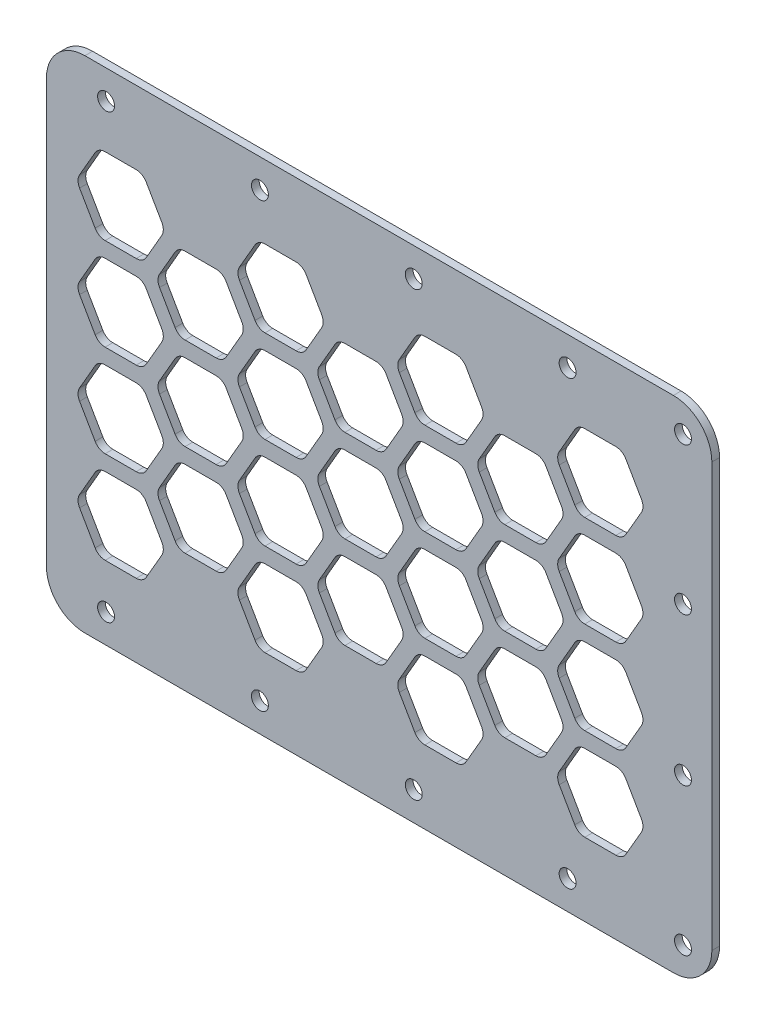
SolidWorks part; units mm, degrees
ref_plane "前视基准面" through (0, 0, 0) normal (0, 0, 1) x (1, 0, 0)
ref_plane "上视基准面" through (0, 0, 0) normal (0, 1, 0) x (1, 0, 0)
ref_plane "右视基准面" through (0, 0, 0) normal (1, 0, 0) x (0, 0, -1)
other "Configuration Table"
sketch "草图1" plane through (0, 0, 0) normal (0, 0, 1) x (1, 0, 0)
  line L1 (0, 0) -> (346, 0)
  line L2 (0, 0) -> (0, -130)
  line L3 (0, -130) -> (346, -130)
  line L4 (346, 0) -> (346, -130)
  dimension "D1" = 346
  dimension "D2" = 130
extrude "凸台-拉伸1" add sketch "草图1" along normal blind 2
sketch "草图2" plane through (0, 0, 2) normal (0, 0, 1) x (1, 0, 0)
  line L0 (15, 0) -> (15, -130)
  line L1 (173, 0) -> (173, -130) construction
  line L2 (331, 0) -> (331, -130)
  line L3 (0, -65) -> (346, -65) construction
  line L4 (0, 0) -> (0, -130)
  line L5 (0, -130) -> (346, -130)
  line L6 (346, -130) -> (346, 0)
  line L7 (346, 0) -> (0, 0)
  line L8 (0, 0) -> (0, -130)
  line L9 (0, -130) -> (346, -130)
  line L10 (346, -130) -> (346, 0)
  line L11 (346, 0) -> (0, 0)
  line L12 (0, -15) -> (346, -15)
  line L13 (0, -115) -> (346, -115)
  line L14 (0, -7.5) -> (346, -7.5) construction
  line L15 (7.5022, -130) -> (7.5022, 0) construction
  line L16 (0, -122.5) -> (346, -122.5) construction
  line L17 (338.5, -130) -> (338.5, 0) construction
  circle A0 centre (7.5022, -45.75) radius 2.2
  circle A1 centre (7.5022, -84.25) radius 2.2
  circle A2 centre (7.5022, -122.5) radius 2.2
  circle A3 centre (37.5022, -122.5) radius 2.2
  circle A4 centre (77.5022, -122.5) radius 2.2
  circle A5 centre (117.5022, -122.5) radius 2.2
  circle A6 centre (117.5022, -7.5) radius 2.2
  circle A7 centre (77.5022, -7.5) radius 2.2
  circle A8 centre (37.5022, -7.5) radius 2.2
  circle A9 centre (7.5022, -7.5) radius 2.2
  circle A10 centre (308.4978, -122.5) radius 2.2
  circle A11 centre (268.4978, -122.5) radius 2.2
  circle A12 centre (228.4978, -122.5) radius 2.2
  circle A13 centre (228.4978, -7.5) radius 2.2
  circle A14 centre (268.4978, -7.5) radius 2.2
  circle A15 centre (308.4978, -7.5) radius 2.2
  circle A16 centre (338.4978, -7.5) radius 2.2
  circle A17 centre (338.4978, -45.75) radius 2.2
  circle A18 centre (338.4978, -84.25) radius 2.2
  circle A19 centre (338.4978, -122.5) radius 2.2
  circle A20 centre (157.5022, -122.5) radius 2.2
  dimension "D8" = 38.5
  dimension "D9" = 4.4
  dimension "D10" = 30
  dimension "D11" = 40
  dimension "D12" = 40
  dimension "D13" = 40
  dimension "D2" = 15
  dimension "D3" = 15
  dimension "D4" = 7.5022
  dimension "D5" = 7.5
  dimension "D6" = 7.5
  dimension "D7" = 7.5
  dimension "D1" = 0
extrude "切除-拉伸1" cut sketch "草图2" against normal blind 33 contours A2 | A3 | A4 | A5 | A12 | A11 | A10 | A19 | A18 | A17 | A16 | A15 | A14 | A13 | A6 | A7 | A9 | A8 | A0 | A1 region at (7.5022, -45.75, 2) region at (7.5022, -84.25, 2) region at (7.5022, -122.5, 2) region at (37.5022, -122.5, 2) region at (77.5022, -122.5, 2) region at (117.5022, -122.5, 2) region at (117.5022, -7.5, 2) region at (77.5022, -7.5, 2) region at (37.5022, -7.5, 2) region at (7.5022, -7.5, 2) region at (308.4978, -122.5, 2) region at (268.4978, -122.5, 2) region at (228.4978, -122.5, 2) region at (228.4978, -7.5, 2) region at (268.4978, -7.5, 2) region at (308.4978, -7.5, 2) region at (338.4978, -7.5, 2) region at (338.4978, -45.75, 2) region at (338.4978, -84.25, 2) region at (338.4978, -122.5, 2)
sketch "草图3" plane through (0, 0, 2) normal (0, 0, 1) x (1, 0, 0)
  line L0 (0, -65) -> (346, -65) construction
  line L1 (173, 0) -> (173, -130) construction
  line L2 (102.9008, -41) -> (97.1273, -31)
  line L3 (24.9585, -19) -> (326, -19) construction
  line L4 (0, 0) -> (0, -130)
  line L5 (0, -130) -> (346, -130)
  line L6 (346, -130) -> (346, 0)
  line L7 (346, 0) -> (0, 0)
  line L8 (0, 0) -> (0, -130)
  line L9 (0, -130) -> (346, -130)
  line L10 (346, -130) -> (346, 0)
  line L11 (346, 0) -> (0, 0)
  line L12 (20, -19) -> (20, -111) construction
  line L13 (20, -111) -> (326, -111) construction
  line L14 (326, -19) -> (326, -111) construction
  line L15 (39.681, -27.5) -> (34.7735, -19)
  line L16 (34.7735, -19) -> (24.9585, -19)
  line L17 (22.3605, -20.5) -> (18.319, -27.5)
  line L18 (18.319, -30.5) -> (22.3605, -37.5)
  line L19 (24.9585, -39) -> (33.0415, -39)
  line L20 (35.6395, -37.5) -> (39.681, -30.5)
  line L21 (39.681, -51.5) -> (35.6395, -44.5)
  line L22 (33.0415, -43) -> (24.9585, -43)
  line L23 (22.3605, -44.5) -> (18.319, -51.5)
  line L24 (18.319, -54.5) -> (22.3605, -61.5)
  line L25 (24.9585, -63) -> (33.0415, -63)
  line L26 (35.6395, -61.5) -> (39.681, -54.5)
  line L27 (60.4656, -39.5) -> (56.4241, -32.5)
  line L28 (53.8261, -31) -> (45.7432, -31)
  line L29 (43.1451, -32.5) -> (39.1036, -39.5)
  line L30 (39.1036, -42.5) -> (43.1451, -49.5)
  line L31 (45.7432, -51) -> (53.8261, -51)
  line L32 (56.4241, -49.5) -> (60.4656, -42.5)
  line L33 (97.1273, -31) -> (85.5803, -31)
  line L34 (85.5803, -31) -> (80.6728, -39.5)
  line L35 (80.6728, -42.5) -> (85.5803, -51)
  line L36 (85.5803, -51) -> (95.3953, -51)
  line L37 (97.9934, -49.5) -> (102.9008, -41)
  line L38 (81.2502, -27.5) -> (77.2087, -20.5)
  line L39 (74.6107, -19) -> (66.5278, -19)
  line L40 (63.9297, -20.5) -> (59.8882, -27.5)
  line L41 (59.8882, -30.5) -> (63.9297, -37.5)
  line L42 (66.5278, -39) -> (74.6107, -39)
  line L43 (77.2087, -37.5) -> (81.2502, -30.5)
  line L44 (81.2502, -51.5) -> (77.2087, -44.5)
  line L45 (74.6107, -43) -> (66.5278, -43)
  line L46 (63.9297, -44.5) -> (59.8882, -51.5)
  line L47 (59.8882, -54.5) -> (63.9297, -61.5)
  line L48 (66.5278, -63) -> (74.6107, -63)
  line L49 (77.2087, -61.5) -> (81.2502, -54.5)
  line L50 (122.8194, -27.5) -> (118.778, -20.5)
  line L51 (116.1799, -19) -> (108.097, -19)
  line L52 (105.4989, -20.5) -> (101.4575, -27.5)
  line L53 (101.4575, -30.5) -> (105.4989, -37.5)
  line L54 (108.097, -39) -> (116.1799, -39)
  line L55 (118.778, -37.5) -> (122.8194, -30.5)
  line L56 (122.8194, -51.5) -> (118.778, -44.5)
  line L57 (116.1799, -43) -> (108.097, -43)
  line L58 (105.4989, -44.5) -> (101.4575, -51.5)
  line L59 (101.4575, -54.5) -> (105.4989, -61.5)
  line L60 (108.097, -63) -> (116.1799, -63)
  line L61 (118.778, -61.5) -> (122.8194, -54.5)
  line L62 (144.4701, -41) -> (139.5626, -32.5)
  line L63 (136.9645, -31) -> (127.1495, -31)
  line L64 (127.1495, -31) -> (121.376, -41)
  line L65 (121.376, -41) -> (126.2835, -49.5)
  line L66 (128.8816, -51) -> (138.6966, -51)
  line L67 (138.6966, -51) -> (144.4701, -41)
  line L68 (164.3886, -27.5) -> (160.3472, -20.5)
  line L69 (157.7491, -19) -> (149.6662, -19)
  line L70 (147.0681, -20.5) -> (143.0267, -27.5)
  line L71 (143.0267, -30.5) -> (147.0681, -37.5)
  line L72 (149.6662, -39) -> (157.7491, -39)
  line L73 (160.3472, -37.5) -> (164.3886, -30.5)
  line L74 (164.3886, -51.5) -> (160.3472, -44.5)
  line L75 (157.7491, -43) -> (149.6662, -43)
  line L76 (147.0681, -44.5) -> (143.0267, -51.5)
  line L77 (143.0267, -54.5) -> (147.0681, -61.5)
  line L78 (149.6662, -63) -> (157.7491, -63)
  line L79 (160.3472, -61.5) -> (164.3886, -54.5)
  line L86 (185.6528, -61.5) -> (181.6114, -54.5)
  line L87 (196.3338, -63) -> (188.2509, -63)
  line L88 (202.9733, -54.5) -> (198.9319, -61.5)
  line L89 (198.9319, -44.5) -> (202.9733, -51.5)
  line L90 (188.2509, -43) -> (196.3338, -43)
  line L91 (181.6114, -51.5) -> (185.6528, -44.5)
  line L92 (185.6528, -37.5) -> (181.6114, -30.5)
  line L93 (196.3338, -39) -> (188.2509, -39)
  line L94 (202.9733, -30.5) -> (198.9319, -37.5)
  line L95 (198.9319, -20.5) -> (202.9733, -27.5)
  line L96 (188.2509, -19) -> (196.3338, -19)
  line L97 (181.6114, -27.5) -> (185.6528, -20.5)
  line L98 (206.4374, -49.5) -> (202.396, -42.5)
  line L99 (217.1184, -51) -> (209.0355, -51)
  line L100 (223.7579, -42.5) -> (219.7165, -49.5)
  line L101 (219.7165, -32.5) -> (223.7579, -39.5)
  line L102 (209.0355, -31) -> (217.1184, -31)
  line L103 (202.396, -39.5) -> (206.4374, -32.5)
  line L104 (227.222, -61.5) -> (223.1806, -54.5)
  line L105 (237.903, -63) -> (229.8201, -63)
  line L106 (244.5425, -54.5) -> (240.5011, -61.5)
  line L107 (240.5011, -44.5) -> (244.5425, -51.5)
  line L108 (229.8201, -43) -> (237.903, -43)
  line L109 (223.1806, -51.5) -> (227.222, -44.5)
  line L110 (227.222, -37.5) -> (223.1806, -30.5)
  line L111 (237.903, -39) -> (229.8201, -39)
  line L112 (244.5425, -30.5) -> (240.5011, -37.5)
  line L113 (240.5011, -20.5) -> (244.5425, -27.5)
  line L114 (229.8201, -19) -> (237.903, -19)
  line L115 (223.1806, -27.5) -> (227.222, -20.5)
  line L116 (248.0066, -49.5) -> (243.9652, -42.5)
  line L117 (258.6876, -51) -> (250.6047, -51)
  line L118 (265.3272, -42.5) -> (261.2857, -49.5)
  line L119 (261.2857, -32.5) -> (265.3272, -39.5)
  line L120 (250.6047, -31) -> (258.6876, -31)
  line L121 (243.9652, -39.5) -> (248.0066, -32.5)
  line L122 (268.7913, -37.5) -> (264.7498, -30.5)
  line L123 (279.4722, -39) -> (271.3893, -39)
  line L124 (286.1118, -30.5) -> (282.0703, -37.5)
  line L125 (282.0703, -20.5) -> (286.1118, -27.5)
  line L126 (271.3893, -19) -> (279.4722, -19)
  line L127 (264.7498, -27.5) -> (268.7913, -20.5)
  line L128 (268.7913, -61.5) -> (264.7498, -54.5)
  line L129 (279.4722, -63) -> (271.3893, -63)
  line L130 (286.1118, -54.5) -> (282.0703, -61.5)
  line L131 (282.0703, -44.5) -> (286.1118, -51.5)
  line L132 (271.3893, -43) -> (279.4722, -43)
  line L133 (264.7498, -51.5) -> (268.7913, -44.5)
  line L134 (289.5759, -49.5) -> (285.5344, -42.5)
  line L135 (300.2568, -51) -> (292.1739, -51)
  line L136 (306.8964, -42.5) -> (302.8549, -49.5)
  line L137 (302.8549, -32.5) -> (306.8964, -39.5)
  line L138 (292.1739, -31) -> (300.2568, -31)
  line L139 (285.5344, -39.5) -> (289.5759, -32.5)
  line L140 (310.3605, -61.5) -> (306.319, -54.5)
  line L141 (321.0415, -63) -> (312.9585, -63)
  line L142 (327.681, -54.5) -> (323.6395, -61.5)
  line L143 (323.6395, -44.5) -> (327.681, -51.5)
  line L144 (312.9585, -43) -> (321.0415, -43)
  line L145 (306.319, -51.5) -> (310.3605, -44.5)
  line L146 (310.3605, -37.5) -> (306.319, -30.5)
  line L147 (321.0415, -39) -> (312.9585, -39)
  line L148 (327.681, -30.5) -> (323.6395, -37.5)
  line L149 (323.6395, -20.5) -> (327.681, -27.5)
  line L150 (312.9585, -19) -> (321.0415, -19)
  line L151 (306.319, -27.5) -> (310.3605, -20.5)
  line L152 (186.0393, -41) -> (180.2658, -31) [skipped]
  line L153 (180.2658, -31) -> (168.7188, -31) [skipped]
  line L154 (168.7188, -31) -> (162.9453, -41) [skipped]
  line L155 (162.9453, -41) -> (168.7188, -51) [skipped]
  line L156 (168.7188, -51) -> (180.2658, -51) [skipped]
  line L157 (180.2658, -51) -> (186.0393, -41) [skipped]
  line L158 (321.0415, -91) -> (312.9585, -91)
  line L159 (327.681, -99.5) -> (323.6395, -92.5)
  line L160 (323.6395, -109.5) -> (327.681, -102.5)
  line L161 (312.9585, -111) -> (321.0415, -111)
  line L162 (306.319, -102.5) -> (310.3605, -109.5)
  line L163 (310.3605, -92.5) -> (306.319, -99.5)
  line L164 (321.0415, -67) -> (312.9585, -67)
  line L165 (327.681, -75.5) -> (323.6395, -68.5)
  line L166 (323.6395, -85.5) -> (327.681, -78.5)
  line L167 (312.9585, -87) -> (321.0415, -87)
  line L168 (306.319, -78.5) -> (310.3605, -85.5)
  line L169 (310.3605, -68.5) -> (306.319, -75.5)
  line L170 (300.2568, -79) -> (292.1739, -79)
  line L171 (306.8964, -87.5) -> (302.8549, -80.5)
  line L172 (302.8549, -97.5) -> (306.8964, -90.5)
  line L173 (292.1739, -99) -> (300.2568, -99)
  line L174 (285.5344, -90.5) -> (289.5759, -97.5)
  line L175 (289.5759, -80.5) -> (285.5344, -87.5)
  line L176 (279.4722, -91) -> (271.3893, -91)
  line L177 (286.1118, -99.5) -> (282.0703, -92.5)
  line L178 (282.0703, -109.5) -> (286.1118, -102.5)
  line L179 (271.3893, -111) -> (279.4722, -111)
  line L180 (264.7498, -102.5) -> (268.7913, -109.5)
  line L181 (268.7913, -92.5) -> (264.7498, -99.5)
  line L182 (279.4722, -67) -> (271.3893, -67)
  line L183 (286.1118, -75.5) -> (282.0703, -68.5)
  line L184 (282.0703, -85.5) -> (286.1118, -78.5)
  line L185 (271.3893, -87) -> (279.4722, -87)
  line L186 (264.7498, -78.5) -> (268.7913, -85.5)
  line L187 (268.7913, -68.5) -> (264.7498, -75.5)
  line L188 (258.6876, -79) -> (250.6047, -79)
  line L189 (265.3272, -87.5) -> (261.2857, -80.5)
  line L190 (261.2857, -97.5) -> (265.3272, -90.5)
  line L191 (250.6047, -99) -> (258.6876, -99)
  line L192 (243.9652, -90.5) -> (248.0066, -97.5)
  line L193 (248.0066, -80.5) -> (243.9652, -87.5)
  line L194 (237.903, -67) -> (229.8201, -67)
  line L195 (244.5425, -75.5) -> (240.5011, -68.5)
  line L196 (240.5011, -85.5) -> (244.5425, -78.5)
  line L197 (229.8201, -87) -> (237.903, -87)
  line L198 (223.1806, -78.5) -> (227.222, -85.5)
  line L199 (227.222, -68.5) -> (223.1806, -75.5)
  line L200 (237.903, -91) -> (229.8201, -91)
  line L201 (244.5425, -99.5) -> (240.5011, -92.5)
  line L202 (240.5011, -109.5) -> (244.5425, -102.5)
  line L203 (229.8201, -111) -> (237.903, -111)
  line L204 (223.1806, -102.5) -> (227.222, -109.5)
  line L205 (227.222, -92.5) -> (223.1806, -99.5)
  line L206 (217.1184, -79) -> (209.0355, -79)
  line L207 (223.7579, -87.5) -> (219.7165, -80.5)
  line L208 (219.7165, -97.5) -> (223.7579, -90.5)
  line L209 (209.0355, -99) -> (217.1184, -99)
  line L210 (202.396, -90.5) -> (206.4374, -97.5)
  line L211 (206.4374, -80.5) -> (202.396, -87.5)
  line L212 (196.3338, -67) -> (188.2509, -67)
  line L213 (202.9733, -75.5) -> (198.9319, -68.5)
  line L214 (198.9319, -85.5) -> (202.9733, -78.5)
  line L215 (188.2509, -87) -> (196.3338, -87)
  line L216 (181.6114, -78.5) -> (185.6528, -85.5)
  line L217 (185.6528, -68.5) -> (181.6114, -75.5)
  line L218 (196.3338, -91) -> (188.2509, -91)
  line L219 (202.9733, -99.5) -> (198.9319, -92.5)
  line L220 (198.9319, -109.5) -> (202.9733, -102.5)
  line L221 (188.2509, -111) -> (196.3338, -111)
  line L222 (181.6114, -102.5) -> (185.6528, -109.5)
  line L223 (185.6528, -92.5) -> (181.6114, -99.5)
  line L224 (160.3472, -68.5) -> (164.3886, -75.5)
  line L225 (149.6662, -67) -> (157.7491, -67)
  line L226 (143.0267, -75.5) -> (147.0681, -68.5)
  line L227 (147.0681, -85.5) -> (143.0267, -78.5)
  line L228 (157.7491, -87) -> (149.6662, -87)
  line L229 (164.3886, -78.5) -> (160.3472, -85.5)
  line L230 (160.3472, -92.5) -> (164.3886, -99.5)
  line L231 (149.6662, -91) -> (157.7491, -91)
  line L232 (143.0267, -99.5) -> (147.0681, -92.5)
  line L233 (147.0681, -109.5) -> (143.0267, -102.5)
  line L234 (157.7491, -111) -> (149.6662, -111)
  line L235 (164.3886, -102.5) -> (160.3472, -109.5)
  line L236 (138.6966, -79) -> (144.4701, -89)
  line L237 (128.8816, -79) -> (138.6966, -79)
  line L238 (121.376, -89) -> (126.2835, -80.5)
  line L239 (127.1495, -99) -> (121.376, -89)
  line L240 (136.9645, -99) -> (127.1495, -99)
  line L241 (144.4701, -89) -> (139.5626, -97.5)
  line L242 (118.778, -68.5) -> (122.8194, -75.5)
  line L243 (108.097, -67) -> (116.1799, -67)
  line L244 (101.4575, -75.5) -> (105.4989, -68.5)
  line L245 (105.4989, -85.5) -> (101.4575, -78.5)
  line L246 (116.1799, -87) -> (108.097, -87)
  line L247 (122.8194, -78.5) -> (118.778, -85.5)
  line L248 (118.778, -92.5) -> (122.8194, -99.5)
  line L249 (108.097, -91) -> (116.1799, -91)
  line L250 (101.4575, -99.5) -> (105.4989, -92.5)
  line L251 (105.4989, -109.5) -> (101.4575, -102.5)
  line L252 (116.1799, -111) -> (108.097, -111)
  line L253 (122.8194, -102.5) -> (118.778, -109.5)
  line L254 (97.9934, -80.5) -> (102.9008, -89)
  line L255 (85.5803, -79) -> (95.3953, -79)
  line L256 (80.6728, -87.5) -> (85.5803, -79)
  line L257 (85.5803, -99) -> (80.6728, -90.5)
  line L258 (97.1273, -99) -> (85.5803, -99)
  line L259 (102.9008, -89) -> (97.1273, -99)
  line L260 (77.2087, -92.5) -> (81.2502, -99.5)
  line L261 (66.5278, -91) -> (74.6107, -91)
  line L262 (59.8882, -99.5) -> (63.9297, -92.5)
  line L263 (63.9297, -109.5) -> (59.8882, -102.5)
  line L264 (74.6107, -111) -> (66.5278, -111)
  line L265 (81.2502, -102.5) -> (77.2087, -109.5)
  line L266 (77.2087, -68.5) -> (81.2502, -75.5)
  line L267 (66.5278, -67) -> (74.6107, -67)
  line L268 (59.8882, -75.5) -> (63.9297, -68.5)
  line L269 (63.9297, -85.5) -> (59.8882, -78.5)
  line L270 (74.6107, -87) -> (66.5278, -87)
  line L271 (81.2502, -78.5) -> (77.2087, -85.5)
  line L272 (56.4241, -80.5) -> (60.4656, -87.5)
  line L273 (45.7432, -79) -> (53.8261, -79)
  line L274 (39.1036, -87.5) -> (43.1451, -80.5)
  line L275 (43.1451, -97.5) -> (39.1036, -90.5)
  line L276 (53.8261, -99) -> (45.7432, -99)
  line L277 (60.4656, -90.5) -> (56.4241, -97.5)
  line L278 (35.6395, -68.5) -> (39.681, -75.5)
  line L279 (24.9585, -67) -> (33.0415, -67)
  line L280 (18.319, -75.5) -> (22.3605, -68.5)
  line L281 (22.3605, -85.5) -> (18.319, -78.5)
  line L282 (33.0415, -87) -> (24.9585, -87)
  line L283 (39.681, -78.5) -> (35.6395, -85.5)
  line L284 (35.6395, -92.5) -> (39.681, -99.5)
  line L285 (24.9585, -91) -> (33.0415, -91)
  line L286 (18.319, -99.5) -> (22.3605, -92.5)
  line L287 (22.3605, -109.5) -> (18.319, -102.5)
  line L288 (34.7735, -111) -> (24.9585, -111)
  line L289 (39.681, -102.5) -> (34.7735, -111)
  circle A0 centre (29, -29) radius 10 construction
  circle A1 centre (29, -53) radius 10 construction
  circle A2 centre (49.7846, -41) radius 10 construction
  arc A3 (24.9585, -19) -> (22.3605, -20.5) centre (24.9585, -22) ccw
  arc A4 (306.319, -54.5) -> (306.319, -51.5) centre (308.9171, -53) cw
  arc A5 (310.3605, -61.5) -> (312.9585, -63) centre (312.9585, -60) ccw
  arc A6 (321.0415, -63) -> (323.6395, -61.5) centre (321.0415, -60) ccw
  arc A7 (327.681, -54.5) -> (327.681, -51.5) centre (325.0829, -53) ccw
  arc A8 (323.6395, -44.5) -> (321.0415, -43) centre (321.0415, -46) ccw
  arc A9 (312.9585, -43) -> (310.3605, -44.5) centre (312.9585, -46) ccw
  arc A10 (306.319, -30.5) -> (306.319, -27.5) centre (308.9171, -29) cw
  arc A11 (310.3605, -37.5) -> (312.9585, -39) centre (312.9585, -36) ccw
  arc A12 (321.0415, -39) -> (323.6395, -37.5) centre (321.0415, -36) ccw
  arc A13 (327.681, -30.5) -> (327.681, -27.5) centre (325.0829, -29) ccw
  arc A14 (323.6395, -20.5) -> (321.0415, -19) centre (321.0415, -22) ccw
  arc A15 (312.9585, -19) -> (310.3605, -20.5) centre (312.9585, -22) ccw
  arc A16 (292.1739, -31) -> (289.5759, -32.5) centre (292.1739, -34) ccw
  arc A17 (302.8549, -32.5) -> (300.2568, -31) centre (300.2568, -34) ccw
  arc A18 (306.8964, -42.5) -> (306.8964, -39.5) centre (304.2983, -41) ccw
  arc A19 (300.2568, -51) -> (302.8549, -49.5) centre (300.2568, -48) ccw
  arc A20 (289.5759, -49.5) -> (292.1739, -51) centre (292.1739, -48) ccw
  arc A21 (285.5344, -42.5) -> (285.5344, -39.5) centre (288.1325, -41) cw
  arc A22 (282.0703, -44.5) -> (279.4722, -43) centre (279.4722, -46) ccw
  arc A23 (286.1118, -54.5) -> (286.1118, -51.5) centre (283.5137, -53) ccw
  arc A24 (279.4722, -63) -> (282.0703, -61.5) centre (279.4722, -60) ccw
  arc A25 (268.7913, -61.5) -> (271.3893, -63) centre (271.3893, -60) ccw
  arc A26 (264.7498, -54.5) -> (264.7498, -51.5) centre (267.3479, -53) cw
  arc A27 (271.3893, -43) -> (268.7913, -44.5) centre (271.3893, -46) ccw
  arc A28 (268.7913, -37.5) -> (271.3893, -39) centre (271.3893, -36) ccw
  arc A29 (279.4722, -39) -> (282.0703, -37.5) centre (279.4722, -36) ccw
  arc A30 (286.1118, -30.5) -> (286.1118, -27.5) centre (283.5137, -29) ccw
  arc A31 (282.0703, -20.5) -> (279.4722, -19) centre (279.4722, -22) ccw
  arc A32 (271.3893, -19) -> (268.7913, -20.5) centre (271.3893, -22) ccw
  arc A33 (264.7498, -30.5) -> (264.7498, -27.5) centre (267.3479, -29) cw
  arc A34 (248.0066, -49.5) -> (250.6047, -51) centre (250.6047, -48) ccw
  arc A35 (258.6876, -51) -> (261.2857, -49.5) centre (258.6876, -48) ccw
  arc A36 (265.3272, -42.5) -> (265.3272, -39.5) centre (262.7291, -41) ccw
  arc A37 (261.2857, -32.5) -> (258.6876, -31) centre (258.6876, -34) ccw
  arc A38 (250.6047, -31) -> (248.0066, -32.5) centre (250.6047, -34) ccw
  arc A39 (243.9652, -42.5) -> (243.9652, -39.5) centre (246.5633, -41) cw
  arc A40 (237.903, -39) -> (240.5011, -37.5) centre (237.903, -36) ccw
  arc A41 (244.5425, -30.5) -> (244.5425, -27.5) centre (241.9445, -29) ccw
  arc A42 (240.5011, -20.5) -> (237.903, -19) centre (237.903, -22) ccw
  arc A43 (229.8201, -19) -> (227.222, -20.5) centre (229.8201, -22) ccw
  arc A44 (227.222, -37.5) -> (229.8201, -39) centre (229.8201, -36) ccw
  arc A45 (223.1806, -30.5) -> (223.1806, -27.5) centre (225.7787, -29) cw
  arc A46 (227.222, -61.5) -> (229.8201, -63) centre (229.8201, -60) ccw
  arc A47 (237.903, -63) -> (240.5011, -61.5) centre (237.903, -60) ccw
  arc A48 (244.5425, -54.5) -> (244.5425, -51.5) centre (241.9445, -53) ccw
  arc A49 (240.5011, -44.5) -> (237.903, -43) centre (237.903, -46) ccw
  arc A50 (229.8201, -43) -> (227.222, -44.5) centre (229.8201, -46) ccw
  arc A51 (223.1806, -54.5) -> (223.1806, -51.5) centre (225.7787, -53) cw
  arc A52 (206.4374, -49.5) -> (209.0355, -51) centre (209.0355, -48) ccw
  arc A53 (217.1184, -51) -> (219.7165, -49.5) centre (217.1184, -48) ccw
  arc A54 (223.7579, -42.5) -> (223.7579, -39.5) centre (221.1599, -41) ccw
  arc A55 (219.7165, -32.5) -> (217.1184, -31) centre (217.1184, -34) ccw
  arc A56 (209.0355, -31) -> (206.4374, -32.5) centre (209.0355, -34) ccw
  arc A57 (202.396, -42.5) -> (202.396, -39.5) centre (204.994, -41) cw
  arc A58 (196.3338, -63) -> (198.9319, -61.5) centre (196.3338, -60) ccw
  arc A59 (185.6528, -61.5) -> (188.2509, -63) centre (188.2509, -60) ccw
  arc A60 (181.6114, -54.5) -> (181.6114, -51.5) centre (184.2094, -53) cw
  arc A61 (198.9319, -44.5) -> (196.3338, -43) centre (196.3338, -46) ccw
  arc A62 (202.9733, -54.5) -> (202.9733, -51.5) centre (200.3752, -53) ccw
  arc A63 (77.2087, -20.5) -> (74.6107, -19) centre (74.6107, -22) ccw
  arc A64 (66.5278, -19) -> (63.9297, -20.5) centre (66.5278, -22) ccw
  arc A65 (160.3472, -20.5) -> (157.7491, -19) centre (157.7491, -22) ccw
  arc A66 (149.6662, -19) -> (147.0681, -20.5) centre (149.6662, -22) ccw
  arc A67 (118.778, -20.5) -> (116.1799, -19) centre (116.1799, -22) ccw
  arc A68 (108.097, -19) -> (105.4989, -20.5) centre (108.097, -22) ccw
  arc A69 (185.6528, -37.5) -> (188.2509, -39) centre (188.2509, -36) ccw
  arc A70 (196.3338, -39) -> (198.9319, -37.5) centre (196.3338, -36) ccw
  arc A71 (202.9733, -30.5) -> (202.9733, -27.5) centre (200.3752, -29) ccw
  arc A72 (198.9319, -20.5) -> (196.3338, -19) centre (196.3338, -22) ccw
  arc A73 (188.2509, -19) -> (185.6528, -20.5) centre (188.2509, -22) ccw
  arc A74 (181.6114, -30.5) -> (181.6114, -27.5) centre (184.2094, -29) cw
  arc A75 (188.2509, -43) -> (185.6528, -44.5) centre (188.2509, -46) ccw
  arc A76 (149.6662, -43) -> (147.0681, -44.5) centre (149.6662, -46) ccw
  arc A77 (143.0267, -51.5) -> (143.0267, -54.5) centre (145.6248, -53) ccw
  arc A78 (147.0681, -61.5) -> (149.6662, -63) centre (149.6662, -60) ccw
  arc A79 (157.7491, -63) -> (160.3472, -61.5) centre (157.7491, -60) ccw
  arc A80 (164.3886, -51.5) -> (164.3886, -54.5) centre (161.7906, -53) cw
  arc A81 (160.3472, -44.5) -> (157.7491, -43) centre (157.7491, -46) ccw
  arc A82 (164.3886, -27.5) -> (164.3886, -30.5) centre (161.7906, -29) cw
  arc A83 (157.7491, -39) -> (160.3472, -37.5) centre (157.7491, -36) ccw
  arc A84 (149.6662, -39) -> (147.0681, -37.5) centre (149.6662, -36) cw
  arc A85 (143.0267, -30.5) -> (143.0267, -27.5) centre (145.6248, -29) cw
  arc A86 (139.5626, -32.5) -> (136.9645, -31) centre (136.9645, -34) ccw
  arc A87 (126.2835, -49.5) -> (128.8816, -51) centre (128.8816, -48) ccw
  arc A88 (118.778, -44.5) -> (116.1799, -43) centre (116.1799, -46) ccw
  arc A89 (122.8194, -54.5) -> (122.8194, -51.5) centre (120.2213, -53) ccw
  arc A90 (116.1799, -63) -> (118.778, -61.5) centre (116.1799, -60) ccw
  arc A91 (108.097, -63) -> (105.4989, -61.5) centre (108.097, -60) cw
  arc A92 (101.4575, -51.5) -> (101.4575, -54.5) centre (104.0555, -53) ccw
  arc A93 (105.4989, -44.5) -> (108.097, -43) centre (108.097, -46) cw
  arc A94 (122.8194, -30.5) -> (122.8194, -27.5) centre (120.2213, -29) ccw
  arc A95 (116.1799, -39) -> (118.778, -37.5) centre (116.1799, -36) ccw
  arc A96 (105.4989, -37.5) -> (108.097, -39) centre (108.097, -36) ccw
  arc A97 (101.4575, -30.5) -> (101.4575, -27.5) centre (104.0555, -29) cw
  arc A98 (80.6728, -42.5) -> (80.6728, -39.5) centre (83.2709, -41) cw
  arc A99 (95.3953, -51) -> (97.9934, -49.5) centre (95.3953, -48) ccw
  arc A100 (81.2502, -30.5) -> (81.2502, -27.5) centre (78.6521, -29) ccw
  arc A101 (74.6107, -39) -> (77.2087, -37.5) centre (74.6107, -36) ccw
  arc A102 (66.5278, -39) -> (63.9297, -37.5) centre (66.5278, -36) cw
  arc A103 (59.8882, -30.5) -> (59.8882, -27.5) centre (62.4863, -29) cw
  arc A104 (66.5278, -43) -> (63.9297, -44.5) centre (66.5278, -46) ccw
  arc A105 (77.2087, -44.5) -> (74.6107, -43) centre (74.6107, -46) ccw
  arc A106 (81.2502, -54.5) -> (81.2502, -51.5) centre (78.6521, -53) ccw
  arc A107 (74.6107, -63) -> (77.2087, -61.5) centre (74.6107, -60) ccw
  arc A108 (66.5278, -63) -> (63.9297, -61.5) centre (66.5278, -60) cw
  arc A109 (59.8882, -54.5) -> (59.8882, -51.5) centre (62.4863, -53) cw
  arc A110 (43.1451, -32.5) -> (45.7432, -31) centre (45.7432, -34) cw
  arc A111 (60.4656, -42.5) -> (60.4656, -39.5) centre (57.8675, -41) ccw
  arc A112 (56.4241, -32.5) -> (53.8261, -31) centre (53.8261, -34) ccw
  arc A113 (53.8261, -51) -> (56.4241, -49.5) centre (53.8261, -48) ccw
  arc A114 (45.7432, -51) -> (43.1451, -49.5) centre (45.7432, -48) cw
  arc A115 (39.1036, -42.5) -> (39.1036, -39.5) centre (41.7017, -41) cw
  arc A116 (35.6395, -44.5) -> (33.0415, -43) centre (33.0415, -46) ccw
  arc A117 (39.681, -51.5) -> (39.681, -54.5) centre (37.0829, -53) cw
  arc A118 (35.6395, -61.5) -> (33.0415, -63) centre (33.0415, -60) cw
  arc A119 (24.9585, -63) -> (22.3605, -61.5) centre (24.9585, -60) cw
  arc A120 (18.319, -54.5) -> (18.319, -51.5) centre (20.9171, -53) cw
  arc A121 (22.3605, -44.5) -> (24.9585, -43) centre (24.9585, -46) cw
  arc A122 (18.319, -27.5) -> (18.319, -30.5) centre (20.9171, -29) ccw
  arc A123 (22.3605, -37.5) -> (24.9585, -39) centre (24.9585, -36) ccw
  arc A124 (33.0415, -39) -> (35.6395, -37.5) centre (33.0415, -36) ccw
  arc A125 (39.681, -30.5) -> (39.681, -27.5) centre (37.0829, -29) ccw
  arc A126 (22.3605, -20.5) -> (24.9585, -19) centre (24.9585, -22) cw
  arc A127 (321.0415, -91) -> (323.6395, -92.5) centre (321.0415, -94) cw
  arc A128 (327.681, -99.5) -> (327.681, -102.5) centre (325.0829, -101) cw
  arc A129 (323.6395, -109.5) -> (321.0415, -111) centre (321.0415, -108) cw
  arc A130 (312.9585, -111) -> (310.3605, -109.5) centre (312.9585, -108) cw
  arc A131 (306.319, -99.5) -> (306.319, -102.5) centre (308.9171, -101) ccw
  arc A132 (310.3605, -92.5) -> (312.9585, -91) centre (312.9585, -94) cw
  arc A133 (321.0415, -67) -> (323.6395, -68.5) centre (321.0415, -70) cw
  arc A134 (327.681, -75.5) -> (327.681, -78.5) centre (325.0829, -77) cw
  arc A135 (323.6395, -85.5) -> (321.0415, -87) centre (321.0415, -84) cw
  arc A136 (312.9585, -87) -> (310.3605, -85.5) centre (312.9585, -84) cw
  arc A137 (306.319, -75.5) -> (306.319, -78.5) centre (308.9171, -77) ccw
  arc A138 (310.3605, -68.5) -> (312.9585, -67) centre (312.9585, -70) cw
  arc A139 (300.2568, -79) -> (302.8549, -80.5) centre (300.2568, -82) cw
  arc A140 (306.8964, -87.5) -> (306.8964, -90.5) centre (304.2983, -89) cw
  arc A141 (302.8549, -97.5) -> (300.2568, -99) centre (300.2568, -96) cw
  arc A142 (292.1739, -99) -> (289.5759, -97.5) centre (292.1739, -96) cw
  arc A143 (289.5759, -80.5) -> (292.1739, -79) centre (292.1739, -82) cw
  arc A144 (285.5344, -87.5) -> (285.5344, -90.5) centre (288.1325, -89) ccw
  arc A145 (279.4722, -91) -> (282.0703, -92.5) centre (279.4722, -94) cw
  arc A146 (286.1118, -99.5) -> (286.1118, -102.5) centre (283.5137, -101) cw
  arc A147 (282.0703, -109.5) -> (279.4722, -111) centre (279.4722, -108) cw
  arc A148 (271.3893, -111) -> (268.7913, -109.5) centre (271.3893, -108) cw
  arc A149 (268.7913, -92.5) -> (271.3893, -91) centre (271.3893, -94) cw
  arc A150 (264.7498, -99.5) -> (264.7498, -102.5) centre (267.3479, -101) ccw
  arc A151 (279.4722, -67) -> (282.0703, -68.5) centre (279.4722, -70) cw
  arc A152 (286.1118, -75.5) -> (286.1118, -78.5) centre (283.5137, -77) cw
  arc A153 (282.0703, -85.5) -> (279.4722, -87) centre (279.4722, -84) cw
  arc A154 (271.3893, -87) -> (268.7913, -85.5) centre (271.3893, -84) cw
  arc A155 (268.7913, -68.5) -> (271.3893, -67) centre (271.3893, -70) cw
  arc A156 (264.7498, -75.5) -> (264.7498, -78.5) centre (267.3479, -77) ccw
  arc A157 (258.6876, -79) -> (261.2857, -80.5) centre (258.6876, -82) cw
  arc A158 (265.3272, -87.5) -> (265.3272, -90.5) centre (262.7291, -89) cw
  arc A159 (261.2857, -97.5) -> (258.6876, -99) centre (258.6876, -96) cw
  arc A160 (250.6047, -99) -> (248.0066, -97.5) centre (250.6047, -96) cw
  arc A161 (248.0066, -80.5) -> (250.6047, -79) centre (250.6047, -82) cw
  arc A162 (243.9652, -87.5) -> (243.9652, -90.5) centre (246.5633, -89) ccw
  arc A163 (237.903, -67) -> (240.5011, -68.5) centre (237.903, -70) cw
  arc A164 (244.5425, -75.5) -> (244.5425, -78.5) centre (241.9445, -77) cw
  arc A165 (240.5011, -85.5) -> (237.903, -87) centre (237.903, -84) cw
  arc A166 (229.8201, -87) -> (227.222, -85.5) centre (229.8201, -84) cw
  arc A167 (227.222, -68.5) -> (229.8201, -67) centre (229.8201, -70) cw
  arc A168 (223.1806, -75.5) -> (223.1806, -78.5) centre (225.7787, -77) ccw
  arc A169 (237.903, -91) -> (240.5011, -92.5) centre (237.903, -94) cw
  arc A170 (244.5425, -99.5) -> (244.5425, -102.5) centre (241.9445, -101) cw
  arc A171 (240.5011, -109.5) -> (237.903, -111) centre (237.903, -108) cw
  arc A172 (229.8201, -111) -> (227.222, -109.5) centre (229.8201, -108) cw
  arc A173 (227.222, -92.5) -> (229.8201, -91) centre (229.8201, -94) cw
  arc A174 (223.1806, -99.5) -> (223.1806, -102.5) centre (225.7787, -101) ccw
  arc A175 (217.1184, -79) -> (219.7165, -80.5) centre (217.1184, -82) cw
  arc A176 (223.7579, -87.5) -> (223.7579, -90.5) centre (221.1599, -89) cw
  arc A177 (219.7165, -97.5) -> (217.1184, -99) centre (217.1184, -96) cw
  arc A178 (209.0355, -99) -> (206.4374, -97.5) centre (209.0355, -96) cw
  arc A179 (206.4374, -80.5) -> (209.0355, -79) centre (209.0355, -82) cw
  arc A180 (202.396, -87.5) -> (202.396, -90.5) centre (204.994, -89) ccw
  arc A181 (196.3338, -67) -> (198.9319, -68.5) centre (196.3338, -70) cw
  arc A182 (202.9733, -75.5) -> (202.9733, -78.5) centre (200.3752, -77) cw
  arc A183 (198.9319, -85.5) -> (196.3338, -87) centre (196.3338, -84) cw
  arc A184 (188.2509, -87) -> (185.6528, -85.5) centre (188.2509, -84) cw
  arc A185 (185.6528, -68.5) -> (188.2509, -67) centre (188.2509, -70) cw
  arc A186 (181.6114, -75.5) -> (181.6114, -78.5) centre (184.2094, -77) ccw
  arc A187 (196.3338, -91) -> (198.9319, -92.5) centre (196.3338, -94) cw
  arc A188 (202.9733, -99.5) -> (202.9733, -102.5) centre (200.3752, -101) cw
  arc A189 (198.9319, -109.5) -> (196.3338, -111) centre (196.3338, -108) cw
  arc A190 (188.2509, -111) -> (185.6528, -109.5) centre (188.2509, -108) cw
  arc A191 (185.6528, -92.5) -> (188.2509, -91) centre (188.2509, -94) cw
  arc A192 (181.6114, -99.5) -> (181.6114, -102.5) centre (184.2094, -101) ccw
  arc A193 (157.7491, -67) -> (160.3472, -68.5) centre (157.7491, -70) cw
  arc A194 (147.0681, -68.5) -> (149.6662, -67) centre (149.6662, -70) cw
  arc A195 (143.0267, -78.5) -> (143.0267, -75.5) centre (145.6248, -77) cw
  arc A196 (149.6662, -87) -> (147.0681, -85.5) centre (149.6662, -84) cw
  arc A197 (164.3886, -78.5) -> (164.3886, -75.5) centre (161.7906, -77) ccw
  arc A198 (160.3472, -85.5) -> (157.7491, -87) centre (157.7491, -84) cw
  arc A199 (157.7491, -91) -> (160.3472, -92.5) centre (157.7491, -94) cw
  arc A200 (149.6662, -91) -> (147.0681, -92.5) centre (149.6662, -94) ccw
  arc A201 (143.0267, -99.5) -> (143.0267, -102.5) centre (145.6248, -101) ccw
  arc A202 (149.6662, -111) -> (147.0681, -109.5) centre (149.6662, -108) cw
  arc A203 (160.3472, -109.5) -> (157.7491, -111) centre (157.7491, -108) cw
  arc A204 (164.3886, -102.5) -> (164.3886, -99.5) centre (161.7906, -101) ccw
  arc A205 (126.2835, -80.5) -> (128.8816, -79) centre (128.8816, -82) cw
  arc A206 (139.5626, -97.5) -> (136.9645, -99) centre (136.9645, -96) cw
  arc A207 (116.1799, -67) -> (118.778, -68.5) centre (116.1799, -70) cw
  arc A208 (108.097, -67) -> (105.4989, -68.5) centre (108.097, -70) ccw
  arc A209 (101.4575, -78.5) -> (101.4575, -75.5) centre (104.0555, -77) cw
  arc A210 (105.4989, -85.5) -> (108.097, -87) centre (108.097, -84) ccw
  arc A211 (118.778, -85.5) -> (116.1799, -87) centre (116.1799, -84) cw
  arc A212 (122.8194, -75.5) -> (122.8194, -78.5) centre (120.2213, -77) cw
  arc A213 (116.1799, -91) -> (118.778, -92.5) centre (116.1799, -94) cw
  arc A214 (105.4989, -92.5) -> (108.097, -91) centre (108.097, -94) cw
  arc A215 (101.4575, -99.5) -> (101.4575, -102.5) centre (104.0555, -101) ccw
  arc A216 (108.097, -111) -> (105.4989, -109.5) centre (108.097, -108) cw
  arc A217 (118.778, -109.5) -> (116.1799, -111) centre (116.1799, -108) cw
  arc A218 (122.8194, -99.5) -> (122.8194, -102.5) centre (120.2213, -101) cw
  arc A219 (95.3953, -79) -> (97.9934, -80.5) centre (95.3953, -82) cw
  arc A220 (80.6728, -87.5) -> (80.6728, -90.5) centre (83.2709, -89) ccw
  arc A221 (74.6107, -91) -> (77.2087, -92.5) centre (74.6107, -94) cw
  arc A222 (66.5278, -91) -> (63.9297, -92.5) centre (66.5278, -94) ccw
  arc A223 (59.8882, -99.5) -> (59.8882, -102.5) centre (62.4863, -101) ccw
  arc A224 (66.5278, -111) -> (63.9297, -109.5) centre (66.5278, -108) cw
  arc A225 (77.2087, -109.5) -> (74.6107, -111) centre (74.6107, -108) cw
  arc A226 (81.2502, -99.5) -> (81.2502, -102.5) centre (78.6521, -101) cw
  arc A227 (74.6107, -67) -> (77.2087, -68.5) centre (74.6107, -70) cw
  arc A228 (66.5278, -67) -> (63.9297, -68.5) centre (66.5278, -70) ccw
  arc A229 (59.8882, -75.5) -> (59.8882, -78.5) centre (62.4863, -77) ccw
  arc A230 (66.5278, -87) -> (63.9297, -85.5) centre (66.5278, -84) cw
  arc A231 (77.2087, -85.5) -> (74.6107, -87) centre (74.6107, -84) cw
  arc A232 (81.2502, -75.5) -> (81.2502, -78.5) centre (78.6521, -77) cw
  arc A233 (53.8261, -79) -> (56.4241, -80.5) centre (53.8261, -82) cw
  arc A234 (45.7432, -79) -> (43.1451, -80.5) centre (45.7432, -82) ccw
  arc A235 (39.1036, -87.5) -> (39.1036, -90.5) centre (41.7017, -89) ccw
  arc A236 (43.1451, -97.5) -> (45.7432, -99) centre (45.7432, -96) ccw
  arc A237 (60.4656, -87.5) -> (60.4656, -90.5) centre (57.8675, -89) cw
  arc A238 (56.4241, -97.5) -> (53.8261, -99) centre (53.8261, -96) cw
  arc A239 (35.6395, -68.5) -> (33.0415, -67) centre (33.0415, -70) ccw
  arc A240 (24.9585, -67) -> (22.3605, -68.5) centre (24.9585, -70) ccw
  arc A241 (18.319, -75.5) -> (18.319, -78.5) centre (20.9171, -77) ccw
  arc A242 (22.3605, -85.5) -> (24.9585, -87) centre (24.9585, -84) ccw
  arc A243 (35.6395, -85.5) -> (33.0415, -87) centre (33.0415, -84) cw
  arc A244 (39.681, -78.5) -> (39.681, -75.5) centre (37.0829, -77) ccw
  arc A245 (33.0415, -91) -> (35.6395, -92.5) centre (33.0415, -94) cw
  arc A246 (22.3605, -92.5) -> (24.9585, -91) centre (24.9585, -94) cw
  arc A247 (18.319, -102.5) -> (18.319, -99.5) centre (20.9171, -101) cw
  arc A248 (24.9585, -111) -> (22.3605, -109.5) centre (24.9585, -108) cw
  arc A249 (39.681, -99.5) -> (39.681, -102.5) centre (37.0829, -101) cw
  point P30 (41.1244, -36)
  point P88 (23.2265, -19)
  point P91 (305.453, -53)
  point P171 (311.2265, -63)
  point P174 (322.7735, -63)
  point P177 (328.547, -53)
  point P180 (322.7735, -43)
  point P183 (311.2265, -43)
  point P186 (305.453, -29)
  point P189 (311.2265, -39)
  point P192 (322.7735, -39)
  point P195 (328.547, -29)
  point P198 (322.7735, -19)
  point P201 (311.2265, -19)
  point P204 (290.4419, -31)
  point P207 (301.9889, -31)
  point P210 (307.7624, -41)
  point P213 (301.9889, -51)
  point P216 (290.4419, -51)
  point P219 (284.6684, -41)
  point P222 (281.2043, -43)
  point P225 (286.9778, -53)
  point P228 (281.2043, -63)
  point P231 (269.6573, -63)
  point P234 (263.8838, -53)
  point P237 (269.6573, -43)
  point P240 (269.6573, -39)
  point P243 (281.2043, -39)
  point P246 (286.9778, -29)
  point P249 (281.2043, -19)
  point P252 (269.6573, -19)
  point P255 (263.8838, -29)
  point P258 (248.8727, -51)
  point P261 (260.4197, -51)
  point P264 (266.1932, -41)
  point P267 (260.4197, -31)
  point P270 (248.8727, -31)
  point P273 (243.0992, -41)
  point P276 (239.6351, -39)
  point P279 (245.4086, -29)
  point P282 (239.6351, -19)
  point P285 (228.0881, -19)
  point P288 (228.0881, -39)
  point P291 (222.3146, -29)
  point P294 (228.0881, -63)
  point P297 (239.6351, -63)
  point P300 (245.4086, -53)
  point P303 (239.6351, -43)
  point P306 (228.0881, -43)
  point P309 (222.3146, -53)
  point P312 (207.3034, -51)
  point P315 (218.8505, -51)
  point P318 (224.624, -41)
  point P321 (218.8505, -31)
  point P324 (207.3034, -31)
  point P327 (201.5299, -41)
  point P330 (198.0658, -63)
  point P333 (186.5188, -63)
  point P336 (180.7453, -53)
  point P339 (198.0658, -43)
  point P342 (203.8393, -53)
  point P345 (76.3427, -19)
  point P348 (64.7957, -19)
  point P351 (159.4812, -19)
  point P354 (147.9342, -19)
  point P357 (117.9119, -19)
  point P360 (106.3649, -19)
  point P363 (186.5188, -39)
  point P366 (198.0658, -39)
  point P369 (203.8393, -29)
  point P372 (198.0658, -19)
  point P375 (186.5188, -19)
  point P378 (180.7453, -29)
  point P381 (186.5188, -43)
  point P384 (147.9342, -43)
  point P387 (142.1607, -53)
  point P390 (147.9342, -63)
  point P393 (159.4812, -63)
  point P396 (165.2547, -53)
  point P399 (159.4812, -43)
  point P402 (165.2547, -29)
  point P405 (159.4812, -39)
  point P408 (147.9342, -39)
  point P411 (142.1607, -29)
  point P414 (138.6966, -31)
  point P417 (127.1495, -51)
  point P420 (117.9119, -43)
  point P423 (123.6854, -53)
  point P426 (117.9119, -63)
  point P429 (106.3649, -63)
  point P432 (100.5914, -53)
  point P435 (106.3649, -43)
  point P438 (123.6854, -29)
  point P441 (117.9119, -39)
  point P444 (106.3649, -39)
  point P447 (100.5914, -29)
  point P450 (79.8068, -41)
  point P453 (97.1273, -51)
  point P456 (82.1162, -29)
  point P459 (76.3427, -39)
  point P462 (64.7957, -39)
  point P465 (59.0222, -29)
  point P468 (64.7957, -43)
  point P471 (76.3427, -43)
  point P474 (82.1162, -53)
  point P477 (76.3427, -63)
  point P480 (64.7957, -63)
  point P483 (59.0222, -53)
  point P486 (44.0111, -31)
  point P489 (61.3316, -41)
  point P492 (55.5581, -31)
  point P495 (55.5581, -51)
  point P498 (44.0111, -51)
  point P501 (38.2376, -41)
  point P504 (34.7735, -43)
  point P507 (40.547, -53)
  point P510 (34.7735, -63)
  point P513 (23.2265, -63)
  point P516 (17.453, -53)
  point P519 (23.2265, -43)
  point P522 (17.453, -29)
  point P525 (23.2265, -39)
  point P528 (34.7735, -39)
  point P531 (40.547, -29)
  dimension "D15" = 3
  dimension "D2" = 20
  dimension "D3" = 19
  dimension "D4" = 20
  dimension "D6" = 20
  dimension "D7" = 4
  dimension "D8" = 20
  dimension "D9" = 4
  dimension "D10" = 4
  dimension "D12" = 4
  dimension "D13" = 2
  dimension "D14" = 4
  dimension "D1" = 0
  dimension "D11" = 2
extrude "切除-拉伸2" cut sketch "草图3" against normal blind 33 contours L20 A125 L15 L16 A3 L17 A122 L18 A123 L19 A124 | A115 L30 A114 L31 A113 L32 A111 L27 A112 L28 A110 L29 | A121 L23 A120 L24 A119 L25 A118 L26 A117 L21 A116 L22 | A103 L41 A102 L42 A101 L43 A100 L38 A63 L39 A64 L40 | A109 L47 A108 L48 A107 L49 A106 L44 A105 L45 A104 L46 | L36 A99 L37 L2 L33 L34 A98 L35 | A97 L53 A96 L54 A95 L55 A94 L50 A67 L51 A68 L52 | A93 L58 A92 L59 A91 L60 A90 L61 A89 L56 A88 L57 | L65 A87 L66 L67 L62 A86 L63 L64 | A85 L71 A84 L72 A83 L73 A82 L68 A65 L69 A66 L70 | L74 A81 L75 A76 L76 A77 L77 A78 L78 A79 L79 A80 | A74 L92 A69 L93 A70 L94 A71 L95 A72 L96 A73 L97 | L90 A75 L91 A60 L86 A59 L87 A58 L88 A62 L89 A61 | A57 L98 A52 L99 A53 L100 A54 L101 A55 L102 A56 L103 | A45 L110 A44 L111 A40 L112 A41 L113 A42 L114 A43 L115 | A51 L104 A46 L105 A47 L106 A48 L107 A49 L108 A50 L109 | A39 L116 A34 L117 A35 L118 A36 L119 A37 L120 A38 L121 | A33 L122 A28 L123 A29 L124 A30 L125 A31 L126 A32 L127 | L132 A27 L133 A26 L128 A25 L129 A24 L130 A23 L131 A22 | A21 L134 A20 L135 A19 L136 A18 L137 A17 L138 A16 L139 | L150 A15 L151 A10 L146 A11 L147 A12 L148 A13 L149 A14 | L144 A9 L145 A4 L140 A5 L141 A6 L142 A7 L143 A8 | A138 L169 A137 L168 A136 L167 A135 L166 A134 L165 A133 L164 | A132 L163 A131 L162 A130 L161 A129 L160 A128 L159 A127 L158 | L175 A144 L174 A142 L173 A141 L172 A140 L171 A139 L170 A143 | L187 A156 L186 A154 L185 A153 L184 A152 L183 A151 L182 A155 | L181 A150 L180 A148 L179 A147 L178 A146 L177 A145 L176 A149 | L193 A162 L192 A160 L191 A159 L190 A158 L189 A157 L188 A161 | L199 A168 L198 A166 L197 A165 L196 A164 L195 A163 L194 A167 | L205 A174 L204 A172 L203 A171 L202 A170 L201 A169 L200 A173 | L211 A180 L210 A178 L209 A177 L208 A176 L207 A175 L206 A179 | L217 A186 L216 A184 L215 A183 L214 A182 L213 A181 L212 A185 | L223 A192 L222 A190 L221 A189 L220 A188 L219 A187 L218 A191 | A198 L229 A197 L224 A193 L225 A194 L226 A195 L227 A196 L228 | A206 L241 L236 L237 A205 L238 L239 L240 | L235 A204 L230 A199 L231 A200 L232 A201 L233 A202 L234 A203 | A212 L242 A207 L243 A208 L244 A209 L245 A210 L246 A211 L247 | A218 L248 A213 L249 A214 L250 A215 L251 A216 L252 A217 L253 | L256 A220 L257 L258 L259 L254 A219 L255 | A232 L266 A227 L267 A228 L268 A229 L269 A230 L270 A231 L271 | A226 L260 A221 L261 A222 L262 A223 L263 A224 L264 A225 L265 | A238 L277 A237 L272 A233 L273 A234 L274 A235 L275 A236 L276 | L283 A244 L278 A239 L279 A240 L280 A241 L281 A242 L282 A243 | A249 L284 A245 L285 A246 L286 A247 L287 A248 L288 L289 region at (91.3617, -40.9864, 2) region at (29.0079, -28.9864, 2) region at (29, -53, 2) region at (49.7846, -41, 2) region at (70.5692, -29, 2) region at (70.5692, -53, 2) region at (112.1384, -29, 2) region at (112.1384, -53, 2) region at (132.923, -41, 2) region at (153.7077, -29, 2) region at (153.7077, -53, 2) region at (192.2923, -53, 2) region at (192.2923, -29, 2) region at (213.077, -41, 2) region at (233.8616, -53, 2) region at (233.8616, -29, 2) region at (254.6462, -41, 2) region at (275.4308, -29, 2) region at (275.4308, -53, 2) region at (296.2154, -41, 2) region at (317, -53, 2) region at (317, -29, 2) region at (317, -101, 2) region at (317, -77, 2) region at (296.2154, -89, 2) region at (275.4308, -101, 2) region at (275.4308, -77, 2) region at (254.6462, -89, 2) region at (233.8616, -77, 2) region at (233.8616, -101, 2) region at (213.077, -89, 2) region at (192.2923, -77, 2) region at (192.2923, -101, 2) region at (153.7077, -77, 2) region at (153.7077, -101, 2) region at (132.923, -89, 2) region at (112.1384, -77, 2) region at (112.1384, -101, 2) region at (91.3617, -89.0136, 2) region at (70.5692, -101, 2) region at (70.5692, -77, 2) region at (49.7846, -89, 2) region at (29, -77, 2) region at (29.0079, -101.0136, 2)
fillet "圆角1" radius 3 13 edges at (144.4701, -89, 1) (138.6966, -79, 1) (127.1495, -99, 1) (138.6966, -51, 1) (144.4701, -41, 1) (121.376, -41, 1) (127.1495, -31, 1) (97.1273, -31, 1) (85.5803, -31, 1) (34.7735, -19, 1) (85.5803, -99, 1) (97.1273, -99, 1) (34.7735, -111, 1)
sketch "草图4" plane through (0, 0, 2) normal (0, 0, 1) x (1, 0, 0)
  line L0 (34.7735, -19) -> (24.9585, -19) construction
  line L1 (39.681, -27.5) -> (34.7735, -19) construction
  line L2 (35.6395, -37.5) -> (39.681, -30.5) construction
  line L3 (24.9585, -39) -> (33.0415, -39) construction
  line L4 (0, 0) -> (0, -130)
  line L5 (0, -130) -> (346, -130)
  line L6 (346, -130) -> (346, 0)
  line L7 (346, 0) -> (0, 0)
  line L8 (0, 0) -> (0, -130)
  line L9 (0, -130) -> (346, -130)
  line L10 (346, -130) -> (346, 0)
  line L11 (346, 0) -> (0, 0)
  line L12 (18.319, -30.5) -> (22.3605, -37.5) construction
  line L13 (22.3605, -20.5) -> (18.319, -27.5) construction
  line L14 (59.8882, -102.5) -> (63.9297, -109.5)
  line L15 (66.5278, -111) -> (74.6107, -111)
  line L16 (77.2087, -109.5) -> (81.2502, -102.5)
  line L17 (81.2502, -99.5) -> (77.2087, -92.5)
  line L18 (74.6107, -91) -> (66.5278, -91)
  line L19 (63.9297, -92.5) -> (59.8882, -99.5)
  line L20 (59.8882, -102.5) -> (63.9297, -109.5)
  line L21 (66.5278, -111) -> (74.6107, -111)
  line L22 (77.2087, -109.5) -> (81.2502, -102.5)
  line L23 (81.2502, -99.5) -> (77.2087, -92.5)
  line L24 (74.6107, -91) -> (66.5278, -91)
  line L25 (63.9297, -92.5) -> (59.8882, -99.5)
  line L26 (312.9585, -87) -> (321.0415, -87)
  line L27 (306.319, -78.5) -> (310.3605, -85.5)
  line L28 (310.3605, -68.5) -> (306.319, -75.5)
  line L29 (321.0415, -67) -> (312.9585, -67)
  line L30 (327.681, -75.5) -> (323.6395, -68.5)
  line L31 (323.6395, -85.5) -> (327.681, -78.5)
  line L32 (312.9585, -87) -> (321.0415, -87)
  line L33 (306.319, -78.5) -> (310.3605, -85.5)
  line L34 (310.3605, -68.5) -> (306.319, -75.5)
  line L35 (321.0415, -67) -> (312.9585, -67)
  line L36 (327.681, -75.5) -> (323.6395, -68.5)
  line L37 (323.6395, -85.5) -> (327.681, -78.5)
  line L38 (223.1806, -30.5) -> (227.222, -37.5)
  line L39 (229.8201, -39) -> (237.903, -39)
  line L40 (240.5011, -37.5) -> (244.5425, -30.5)
  line L41 (244.5425, -27.5) -> (240.5011, -20.5)
  line L42 (237.903, -19) -> (229.8201, -19)
  line L43 (227.222, -20.5) -> (223.1806, -27.5)
  line L44 (223.1806, -30.5) -> (227.222, -37.5)
  line L45 (229.8201, -39) -> (237.903, -39)
  line L46 (240.5011, -37.5) -> (244.5425, -30.5)
  line L47 (244.5425, -27.5) -> (240.5011, -20.5)
  line L48 (237.903, -19) -> (229.8201, -19)
  line L49 (227.222, -20.5) -> (223.1806, -27.5)
  line L50 (63.9297, -68.5) -> (59.8882, -75.5)
  line L51 (74.6107, -67) -> (66.5278, -67)
  line L52 (81.2502, -75.5) -> (77.2087, -68.5)
  line L53 (77.2087, -85.5) -> (81.2502, -78.5)
  line L54 (66.5278, -87) -> (74.6107, -87)
  line L55 (59.8882, -78.5) -> (63.9297, -85.5)
  line L56 (63.9297, -68.5) -> (59.8882, -75.5)
  line L57 (74.6107, -67) -> (66.5278, -67)
  line L58 (81.2502, -75.5) -> (77.2087, -68.5)
  line L59 (77.2087, -85.5) -> (81.2502, -78.5)
  line L60 (66.5278, -87) -> (74.6107, -87)
  line L61 (59.8882, -78.5) -> (63.9297, -85.5)
  line L62 (302.8549, -97.5) -> (306.8964, -90.5)
  line L63 (306.8964, -87.5) -> (302.8549, -80.5)
  line L64 (300.2568, -79) -> (292.1739, -79)
  line L65 (289.5759, -80.5) -> (285.5344, -87.5)
  line L66 (285.5344, -90.5) -> (289.5759, -97.5)
  line L67 (292.1739, -99) -> (300.2568, -99)
  line L68 (302.8549, -97.5) -> (306.8964, -90.5)
  line L69 (306.8964, -87.5) -> (302.8549, -80.5)
  line L70 (300.2568, -79) -> (292.1739, -79)
  line L71 (289.5759, -80.5) -> (285.5344, -87.5)
  line L72 (285.5344, -90.5) -> (289.5759, -97.5)
  line L73 (292.1739, -99) -> (300.2568, -99)
  line L74 (223.1806, -54.5) -> (227.222, -61.5)
  line L75 (229.8201, -63) -> (237.903, -63)
  line L76 (240.5011, -61.5) -> (244.5425, -54.5)
  line L77 (244.5425, -51.5) -> (240.5011, -44.5)
  line L78 (237.903, -43) -> (229.8201, -43)
  line L79 (227.222, -44.5) -> (223.1806, -51.5)
  line L80 (223.1806, -54.5) -> (227.222, -61.5)
  line L81 (229.8201, -63) -> (237.903, -63)
  line L82 (240.5011, -61.5) -> (244.5425, -54.5)
  line L83 (244.5425, -51.5) -> (240.5011, -44.5)
  line L84 (237.903, -43) -> (229.8201, -43)
  line L85 (227.222, -44.5) -> (223.1806, -51.5)
  line L86 (53.8261, -79) -> (45.7432, -79)
  line L87 (60.4656, -87.5) -> (56.4241, -80.5)
  line L88 (56.4241, -97.5) -> (60.4656, -90.5)
  line L89 (45.7432, -99) -> (53.8261, -99)
  line L90 (39.1036, -90.5) -> (43.1451, -97.5)
  line L91 (43.1451, -80.5) -> (39.1036, -87.5)
  line L92 (53.8261, -79) -> (45.7432, -79)
  line L93 (60.4656, -87.5) -> (56.4241, -80.5)
  line L94 (56.4241, -97.5) -> (60.4656, -90.5)
  line L95 (45.7432, -99) -> (53.8261, -99)
  line L96 (39.1036, -90.5) -> (43.1451, -97.5)
  line L97 (43.1451, -80.5) -> (39.1036, -87.5)
  line L98 (286.1118, -99.5) -> (282.0703, -92.5)
  line L99 (279.4722, -91) -> (271.3893, -91)
  line L100 (268.7913, -92.5) -> (264.7498, -99.5)
  line L101 (264.7498, -102.5) -> (268.7913, -109.5)
  line L102 (271.3893, -111) -> (279.4722, -111)
  line L103 (282.0703, -109.5) -> (286.1118, -102.5)
  line L104 (286.1118, -99.5) -> (282.0703, -92.5)
  line L105 (279.4722, -91) -> (271.3893, -91)
  line L106 (268.7913, -92.5) -> (264.7498, -99.5)
  line L107 (264.7498, -102.5) -> (268.7913, -109.5)
  line L108 (271.3893, -111) -> (279.4722, -111)
  line L109 (282.0703, -109.5) -> (286.1118, -102.5)
  line L110 (202.396, -42.5) -> (206.4374, -49.5)
  line L111 (209.0355, -51) -> (217.1184, -51)
  line L112 (219.7165, -49.5) -> (223.7579, -42.5)
  line L113 (223.7579, -39.5) -> (219.7165, -32.5)
  line L114 (217.1184, -31) -> (209.0355, -31)
  line L115 (206.4374, -32.5) -> (202.396, -39.5)
  line L116 (202.396, -42.5) -> (206.4374, -49.5)
  line L117 (209.0355, -51) -> (217.1184, -51)
  line L118 (219.7165, -49.5) -> (223.7579, -42.5)
  line L119 (223.7579, -39.5) -> (219.7165, -32.5)
  line L120 (217.1184, -31) -> (209.0355, -31)
  line L121 (206.4374, -32.5) -> (202.396, -39.5)
  line L122 (35.6395, -85.5) -> (39.681, -78.5)
  line L123 (24.9585, -87) -> (33.0415, -87)
  line L124 (18.319, -78.5) -> (22.3605, -85.5)
  line L125 (22.3605, -68.5) -> (18.319, -75.5)
  line L126 (33.0415, -67) -> (24.9585, -67)
  line L127 (39.681, -75.5) -> (35.6395, -68.5)
  line L128 (35.6395, -85.5) -> (39.681, -78.5)
  line L129 (24.9585, -87) -> (33.0415, -87)
  line L130 (18.319, -78.5) -> (22.3605, -85.5)
  line L131 (22.3605, -68.5) -> (18.319, -75.5)
  line L132 (33.0415, -67) -> (24.9585, -67)
  line L133 (39.681, -75.5) -> (35.6395, -68.5)
  line L134 (264.7498, -78.5) -> (268.7913, -85.5)
  line L135 (271.3893, -87) -> (279.4722, -87)
  line L136 (282.0703, -85.5) -> (286.1118, -78.5)
  line L137 (286.1118, -75.5) -> (282.0703, -68.5)
  line L138 (279.4722, -67) -> (271.3893, -67)
  line L139 (268.7913, -68.5) -> (264.7498, -75.5)
  line L140 (264.7498, -78.5) -> (268.7913, -85.5)
  line L141 (271.3893, -87) -> (279.4722, -87)
  line L142 (282.0703, -85.5) -> (286.1118, -78.5)
  line L143 (286.1118, -75.5) -> (282.0703, -68.5)
  line L144 (279.4722, -67) -> (271.3893, -67)
  line L145 (268.7913, -68.5) -> (264.7498, -75.5)
  line L146 (39.681, -99.5) -> (35.6395, -92.5)
  line L147 (33.0415, -91) -> (24.9585, -91)
  line L148 (22.3605, -92.5) -> (18.319, -99.5)
  line L149 (18.319, -102.5) -> (22.3605, -109.5)
  line L150 (24.9585, -111) -> (34.7735, -111)
  line L151 (34.7735, -111) -> (39.681, -102.5)
  line L152 (39.681, -99.5) -> (35.6395, -92.5)
  line L153 (33.0415, -91) -> (24.9585, -91)
  line L154 (22.3605, -92.5) -> (18.319, -99.5)
  line L155 (18.319, -102.5) -> (22.3605, -109.5)
  line L156 (24.9585, -111) -> (34.7735, -111)
  line L157 (34.7735, -111) -> (39.681, -102.5)
  line L158 (248.0066, -80.5) -> (243.9652, -87.5)
  line L159 (243.9652, -90.5) -> (248.0066, -97.5)
  line L160 (250.6047, -99) -> (258.6876, -99)
  line L161 (261.2857, -97.5) -> (265.3272, -90.5)
  line L162 (265.3272, -87.5) -> (261.2857, -80.5)
  line L163 (258.6876, -79) -> (250.6047, -79)
  line L164 (248.0066, -80.5) -> (243.9652, -87.5)
  line L165 (243.9652, -90.5) -> (248.0066, -97.5)
  line L166 (250.6047, -99) -> (258.6876, -99)
  line L167 (261.2857, -97.5) -> (265.3272, -90.5)
  line L168 (265.3272, -87.5) -> (261.2857, -80.5)
  line L169 (258.6876, -79) -> (250.6047, -79)
  line L170 (181.6114, -30.5) -> (185.6528, -37.5)
  line L171 (188.2509, -39) -> (196.3338, -39)
  line L172 (198.9319, -37.5) -> (202.9733, -30.5)
  line L173 (202.9733, -27.5) -> (198.9319, -20.5)
  line L174 (196.3338, -19) -> (188.2509, -19)
  line L175 (185.6528, -20.5) -> (181.6114, -27.5)
  line L176 (181.6114, -30.5) -> (185.6528, -37.5)
  line L177 (188.2509, -39) -> (196.3338, -39)
  line L178 (198.9319, -37.5) -> (202.9733, -30.5)
  line L179 (202.9733, -27.5) -> (198.9319, -20.5)
  line L180 (196.3338, -19) -> (188.2509, -19)
  line L181 (185.6528, -20.5) -> (181.6114, -27.5)
  line L182 (196.3338, -43) -> (188.2509, -43)
  line L183 (202.9733, -51.5) -> (198.9319, -44.5)
  line L184 (198.9319, -61.5) -> (202.9733, -54.5)
  line L185 (188.2509, -63) -> (196.3338, -63)
  line L186 (181.6114, -54.5) -> (185.6528, -61.5)
  line L187 (185.6528, -44.5) -> (181.6114, -51.5)
  line L188 (196.3338, -43) -> (188.2509, -43)
  line L189 (202.9733, -51.5) -> (198.9319, -44.5)
  line L190 (198.9319, -61.5) -> (202.9733, -54.5)
  line L191 (188.2509, -63) -> (196.3338, -63)
  line L192 (181.6114, -54.5) -> (185.6528, -61.5)
  line L193 (185.6528, -44.5) -> (181.6114, -51.5)
  line L194 (227.222, -68.5) -> (223.1806, -75.5)
  line L195 (237.903, -67) -> (229.8201, -67)
  line L196 (244.5425, -75.5) -> (240.5011, -68.5)
  line L197 (240.5011, -85.5) -> (244.5425, -78.5)
  line L198 (229.8201, -87) -> (237.903, -87)
  line L199 (223.1806, -78.5) -> (227.222, -85.5)
  line L200 (227.222, -68.5) -> (223.1806, -75.5)
  line L201 (237.903, -67) -> (229.8201, -67)
  line L202 (244.5425, -75.5) -> (240.5011, -68.5)
  line L203 (240.5011, -85.5) -> (244.5425, -78.5)
  line L204 (229.8201, -87) -> (237.903, -87)
  line L205 (223.1806, -78.5) -> (227.222, -85.5)
  line L206 (164.3886, -51.5) -> (160.3472, -44.5)
  line L207 (157.7491, -43) -> (149.6662, -43)
  line L208 (147.0681, -44.5) -> (143.0267, -51.5)
  line L209 (143.0267, -54.5) -> (147.0681, -61.5)
  line L210 (149.6662, -63) -> (157.7491, -63)
  line L211 (160.3472, -61.5) -> (164.3886, -54.5)
  line L212 (164.3886, -51.5) -> (160.3472, -44.5)
  line L213 (157.7491, -43) -> (149.6662, -43)
  line L214 (147.0681, -44.5) -> (143.0267, -51.5)
  line L215 (143.0267, -54.5) -> (147.0681, -61.5)
  line L216 (149.6662, -63) -> (157.7491, -63)
  line L217 (160.3472, -61.5) -> (164.3886, -54.5)
  line L218 (223.1806, -102.5) -> (227.222, -109.5)
  line L219 (229.8201, -111) -> (237.903, -111)
  line L220 (240.5011, -109.5) -> (244.5425, -102.5)
  line L221 (244.5425, -99.5) -> (240.5011, -92.5)
  line L222 (237.903, -91) -> (229.8201, -91)
  line L223 (227.222, -92.5) -> (223.1806, -99.5)
  line L224 (223.1806, -102.5) -> (227.222, -109.5)
  line L225 (229.8201, -111) -> (237.903, -111)
  line L226 (240.5011, -109.5) -> (244.5425, -102.5)
  line L227 (244.5425, -99.5) -> (240.5011, -92.5)
  line L228 (237.903, -91) -> (229.8201, -91)
  line L229 (227.222, -92.5) -> (223.1806, -99.5)
  line L230 (164.3886, -27.5) -> (160.3472, -20.5)
  line L231 (157.7491, -19) -> (149.6662, -19)
  line L232 (147.0681, -20.5) -> (143.0267, -27.5)
  line L233 (143.0267, -30.5) -> (147.0681, -37.5)
  line L234 (149.6662, -39) -> (157.7491, -39)
  line L235 (160.3472, -37.5) -> (164.3886, -30.5)
  line L236 (164.3886, -27.5) -> (160.3472, -20.5)
  line L237 (157.7491, -19) -> (149.6662, -19)
  line L238 (147.0681, -20.5) -> (143.0267, -27.5)
  line L239 (143.0267, -30.5) -> (147.0681, -37.5)
  line L240 (149.6662, -39) -> (157.7491, -39)
  line L241 (160.3472, -37.5) -> (164.3886, -30.5)
  line L242 (209.0355, -99) -> (217.1184, -99)
  line L243 (219.7165, -97.5) -> (223.7579, -90.5)
  line L244 (223.7579, -87.5) -> (219.7165, -80.5)
  line L245 (217.1184, -79) -> (209.0355, -79)
  line L246 (206.4374, -80.5) -> (202.396, -87.5)
  line L247 (202.396, -90.5) -> (206.4374, -97.5)
  line L248 (209.0355, -99) -> (217.1184, -99)
  line L249 (219.7165, -97.5) -> (223.7579, -90.5)
  line L250 (223.7579, -87.5) -> (219.7165, -80.5)
  line L251 (217.1184, -79) -> (209.0355, -79)
  line L252 (206.4374, -80.5) -> (202.396, -87.5)
  line L253 (202.396, -90.5) -> (206.4374, -97.5)
  line L254 (128.8816, -51) -> (138.6966, -51)
  line L255 (138.6966, -51) -> (144.4701, -41)
  line L256 (144.4701, -41) -> (139.5626, -32.5)
  line L257 (136.9645, -31) -> (127.1495, -31)
  line L258 (127.1495, -31) -> (121.376, -41)
  line L259 (121.376, -41) -> (126.2835, -49.5)
  line L260 (128.8816, -51) -> (138.6966, -51)
  line L261 (138.6966, -51) -> (144.4701, -41)
  line L262 (144.4701, -41) -> (139.5626, -32.5)
  line L263 (136.9645, -31) -> (127.1495, -31)
  line L264 (127.1495, -31) -> (121.376, -41)
  line L265 (121.376, -41) -> (126.2835, -49.5)
  line L266 (188.2509, -87) -> (196.3338, -87)
  line L267 (181.6114, -78.5) -> (185.6528, -85.5)
  line L268 (185.6528, -68.5) -> (181.6114, -75.5)
  line L269 (196.3338, -67) -> (188.2509, -67)
  line L270 (202.9733, -75.5) -> (198.9319, -68.5)
  line L271 (198.9319, -85.5) -> (202.9733, -78.5)
  line L272 (188.2509, -87) -> (196.3338, -87)
  line L273 (181.6114, -78.5) -> (185.6528, -85.5)
  line L274 (185.6528, -68.5) -> (181.6114, -75.5)
  line L275 (196.3338, -67) -> (188.2509, -67)
  line L276 (202.9733, -75.5) -> (198.9319, -68.5)
  line L277 (198.9319, -85.5) -> (202.9733, -78.5)
  line L278 (116.1799, -43) -> (108.097, -43)
  line L279 (122.8194, -51.5) -> (118.778, -44.5)
  line L280 (118.778, -61.5) -> (122.8194, -54.5)
  line L281 (108.097, -63) -> (116.1799, -63)
  line L282 (101.4575, -54.5) -> (105.4989, -61.5)
  line L283 (105.4989, -44.5) -> (101.4575, -51.5)
  line L284 (116.1799, -43) -> (108.097, -43)
  line L285 (122.8194, -51.5) -> (118.778, -44.5)
  line L286 (118.778, -61.5) -> (122.8194, -54.5)
  line L287 (108.097, -63) -> (116.1799, -63)
  line L288 (101.4575, -54.5) -> (105.4989, -61.5)
  line L289 (105.4989, -44.5) -> (101.4575, -51.5)
  line L290 (122.8194, -27.5) -> (118.778, -20.5)
  line L291 (116.1799, -19) -> (108.097, -19)
  line L292 (105.4989, -20.5) -> (101.4575, -27.5)
  line L293 (101.4575, -30.5) -> (105.4989, -37.5)
  line L294 (108.097, -39) -> (116.1799, -39)
  line L295 (118.778, -37.5) -> (122.8194, -30.5)
  line L296 (122.8194, -27.5) -> (118.778, -20.5)
  line L297 (116.1799, -19) -> (108.097, -19)
  line L298 (105.4989, -20.5) -> (101.4575, -27.5)
  line L299 (101.4575, -30.5) -> (105.4989, -37.5)
  line L300 (108.097, -39) -> (116.1799, -39)
  line L301 (118.778, -37.5) -> (122.8194, -30.5)
  line L302 (198.9319, -109.5) -> (202.9733, -102.5)
  line L303 (202.9733, -99.5) -> (198.9319, -92.5)
  line L304 (196.3338, -91) -> (188.2509, -91)
  line L305 (185.6528, -92.5) -> (181.6114, -99.5)
  line L306 (181.6114, -102.5) -> (185.6528, -109.5)
  line L307 (188.2509, -111) -> (196.3338, -111)
  line L308 (198.9319, -109.5) -> (202.9733, -102.5)
  line L309 (202.9733, -99.5) -> (198.9319, -92.5)
  line L310 (196.3338, -91) -> (188.2509, -91)
  line L311 (185.6528, -92.5) -> (181.6114, -99.5)
  line L312 (181.6114, -102.5) -> (185.6528, -109.5)
  line L313 (188.2509, -111) -> (196.3338, -111)
  line L314 (327.681, -51.5) -> (323.6395, -44.5)
  line L315 (323.6395, -61.5) -> (327.681, -54.5)
  line L316 (312.9585, -63) -> (321.0415, -63)
  line L317 (306.319, -54.5) -> (310.3605, -61.5)
  line L318 (310.3605, -44.5) -> (306.319, -51.5)
  line L319 (321.0415, -43) -> (312.9585, -43)
  line L320 (327.681, -51.5) -> (323.6395, -44.5)
  line L321 (323.6395, -61.5) -> (327.681, -54.5)
  line L322 (312.9585, -63) -> (321.0415, -63)
  line L323 (306.319, -54.5) -> (310.3605, -61.5)
  line L324 (310.3605, -44.5) -> (306.319, -51.5)
  line L325 (321.0415, -43) -> (312.9585, -43)
  line L326 (85.5803, -31) -> (80.6728, -39.5)
  line L327 (97.1273, -31) -> (85.5803, -31)
  line L328 (102.9008, -41) -> (97.1273, -31)
  line L329 (97.9934, -49.5) -> (102.9008, -41)
  line L330 (85.5803, -51) -> (95.3953, -51)
  line L331 (80.6728, -42.5) -> (85.5803, -51)
  line L332 (85.5803, -31) -> (80.6728, -39.5)
  line L333 (97.1273, -31) -> (85.5803, -31)
  line L334 (102.9008, -41) -> (97.1273, -31)
  line L335 (97.9934, -49.5) -> (102.9008, -41)
  line L336 (85.5803, -51) -> (95.3953, -51)
  line L337 (80.6728, -42.5) -> (85.5803, -51)
  line L338 (157.7491, -67) -> (149.6662, -67)
  line L339 (164.3886, -75.5) -> (160.3472, -68.5)
  line L340 (160.3472, -85.5) -> (164.3886, -78.5)
  line L341 (149.6662, -87) -> (157.7491, -87)
  line L342 (143.0267, -78.5) -> (147.0681, -85.5)
  line L343 (147.0681, -68.5) -> (143.0267, -75.5)
  line L344 (157.7491, -67) -> (149.6662, -67)
  line L345 (164.3886, -75.5) -> (160.3472, -68.5)
  line L346 (160.3472, -85.5) -> (164.3886, -78.5)
  line L347 (149.6662, -87) -> (157.7491, -87)
  line L348 (143.0267, -78.5) -> (147.0681, -85.5)
  line L349 (147.0681, -68.5) -> (143.0267, -75.5)
  line L350 (327.681, -27.5) -> (323.6395, -20.5)
  line L351 (321.0415, -19) -> (312.9585, -19)
  line L352 (310.3605, -20.5) -> (306.319, -27.5)
  line L353 (306.319, -30.5) -> (310.3605, -37.5)
  line L354 (312.9585, -39) -> (321.0415, -39)
  line L355 (323.6395, -37.5) -> (327.681, -30.5)
  line L356 (327.681, -27.5) -> (323.6395, -20.5)
  line L357 (321.0415, -19) -> (312.9585, -19)
  line L358 (310.3605, -20.5) -> (306.319, -27.5)
  line L359 (306.319, -30.5) -> (310.3605, -37.5)
  line L360 (312.9585, -39) -> (321.0415, -39)
  line L361 (323.6395, -37.5) -> (327.681, -30.5)
  line L362 (63.9297, -20.5) -> (59.8882, -27.5)
  line L363 (74.6107, -19) -> (66.5278, -19)
  line L364 (81.2502, -27.5) -> (77.2087, -20.5)
  line L365 (77.2087, -37.5) -> (81.2502, -30.5)
  line L366 (66.5278, -39) -> (74.6107, -39)
  line L367 (59.8882, -30.5) -> (63.9297, -37.5)
  line L368 (63.9297, -20.5) -> (59.8882, -27.5)
  line L369 (74.6107, -19) -> (66.5278, -19)
  line L370 (81.2502, -27.5) -> (77.2087, -20.5)
  line L371 (77.2087, -37.5) -> (81.2502, -30.5)
  line L372 (66.5278, -39) -> (74.6107, -39)
  line L373 (59.8882, -30.5) -> (63.9297, -37.5)
  line L374 (285.5344, -42.5) -> (289.5759, -49.5)
  line L375 (289.5759, -32.5) -> (285.5344, -39.5)
  line L376 (300.2568, -31) -> (292.1739, -31)
  line L377 (306.8964, -39.5) -> (302.8549, -32.5)
  line L378 (302.8549, -49.5) -> (306.8964, -42.5)
  line L379 (292.1739, -51) -> (300.2568, -51)
  line L380 (285.5344, -42.5) -> (289.5759, -49.5)
  line L381 (289.5759, -32.5) -> (285.5344, -39.5)
  line L382 (300.2568, -31) -> (292.1739, -31)
  line L383 (306.8964, -39.5) -> (302.8549, -32.5)
  line L384 (302.8549, -49.5) -> (306.8964, -42.5)
  line L385 (292.1739, -51) -> (300.2568, -51)
  line L386 (63.9297, -44.5) -> (59.8882, -51.5)
  line L387 (74.6107, -43) -> (66.5278, -43)
  line L388 (81.2502, -51.5) -> (77.2087, -44.5)
  line L389 (77.2087, -61.5) -> (81.2502, -54.5)
  line L390 (66.5278, -63) -> (74.6107, -63)
  line L391 (59.8882, -54.5) -> (63.9297, -61.5)
  line L392 (63.9297, -44.5) -> (59.8882, -51.5)
  line L393 (74.6107, -43) -> (66.5278, -43)
  line L394 (81.2502, -51.5) -> (77.2087, -44.5)
  line L395 (77.2087, -61.5) -> (81.2502, -54.5)
  line L396 (66.5278, -63) -> (74.6107, -63)
  line L397 (59.8882, -54.5) -> (63.9297, -61.5)
  line L398 (144.4701, -89) -> (138.6966, -79)
  line L399 (139.5626, -97.5) -> (144.4701, -89)
  line L400 (127.1495, -99) -> (136.9645, -99)
  line L401 (121.376, -89) -> (127.1495, -99)
  line L402 (126.2835, -80.5) -> (121.376, -89)
  line L403 (138.6966, -79) -> (128.8816, -79)
  line L404 (144.4701, -89) -> (138.6966, -79)
  line L405 (139.5626, -97.5) -> (144.4701, -89)
  line L406 (127.1495, -99) -> (136.9645, -99)
  line L407 (121.376, -89) -> (127.1495, -99)
  line L408 (126.2835, -80.5) -> (121.376, -89)
  line L409 (138.6966, -79) -> (128.8816, -79)
  line L410 (160.3472, -109.5) -> (164.3886, -102.5)
  line L411 (149.6662, -111) -> (157.7491, -111)
  line L412 (143.0267, -102.5) -> (147.0681, -109.5)
  line L413 (147.0681, -92.5) -> (143.0267, -99.5)
  line L414 (157.7491, -91) -> (149.6662, -91)
  line L415 (164.3886, -99.5) -> (160.3472, -92.5)
  line L416 (160.3472, -109.5) -> (164.3886, -102.5)
  line L417 (149.6662, -111) -> (157.7491, -111)
  line L418 (143.0267, -102.5) -> (147.0681, -109.5)
  line L419 (147.0681, -92.5) -> (143.0267, -99.5)
  line L420 (157.7491, -91) -> (149.6662, -91)
  line L421 (164.3886, -99.5) -> (160.3472, -92.5)
  line L422 (264.7498, -54.5) -> (268.7913, -61.5)
  line L423 (268.7913, -44.5) -> (264.7498, -51.5)
  line L424 (279.4722, -43) -> (271.3893, -43)
  line L425 (286.1118, -51.5) -> (282.0703, -44.5)
  line L426 (282.0703, -61.5) -> (286.1118, -54.5)
  line L427 (271.3893, -63) -> (279.4722, -63)
  line L428 (264.7498, -54.5) -> (268.7913, -61.5)
  line L429 (268.7913, -44.5) -> (264.7498, -51.5)
  line L430 (279.4722, -43) -> (271.3893, -43)
  line L431 (286.1118, -51.5) -> (282.0703, -44.5)
  line L432 (282.0703, -61.5) -> (286.1118, -54.5)
  line L433 (271.3893, -63) -> (279.4722, -63)
  line L434 (43.1451, -32.5) -> (39.1036, -39.5)
  line L435 (53.8261, -31) -> (45.7432, -31)
  line L436 (60.4656, -39.5) -> (56.4241, -32.5)
  line L437 (56.4241, -49.5) -> (60.4656, -42.5)
  line L438 (45.7432, -51) -> (53.8261, -51)
  line L439 (39.1036, -42.5) -> (43.1451, -49.5)
  line L440 (43.1451, -32.5) -> (39.1036, -39.5)
  line L441 (53.8261, -31) -> (45.7432, -31)
  line L442 (60.4656, -39.5) -> (56.4241, -32.5)
  line L443 (56.4241, -49.5) -> (60.4656, -42.5)
  line L444 (45.7432, -51) -> (53.8261, -51)
  line L445 (39.1036, -42.5) -> (43.1451, -49.5)
  line L446 (105.4989, -68.5) -> (101.4575, -75.5)
  line L447 (116.1799, -67) -> (108.097, -67)
  line L448 (122.8194, -75.5) -> (118.778, -68.5)
  line L449 (118.778, -85.5) -> (122.8194, -78.5)
  line L450 (108.097, -87) -> (116.1799, -87)
  line L451 (101.4575, -78.5) -> (105.4989, -85.5)
  line L452 (105.4989, -68.5) -> (101.4575, -75.5)
  line L453 (116.1799, -67) -> (108.097, -67)
  line L454 (122.8194, -75.5) -> (118.778, -68.5)
  line L455 (118.778, -85.5) -> (122.8194, -78.5)
  line L456 (108.097, -87) -> (116.1799, -87)
  line L457 (101.4575, -78.5) -> (105.4989, -85.5)
  line L458 (264.7498, -30.5) -> (268.7913, -37.5)
  line L459 (271.3893, -39) -> (279.4722, -39)
  line L460 (282.0703, -37.5) -> (286.1118, -30.5)
  line L461 (286.1118, -27.5) -> (282.0703, -20.5)
  line L462 (279.4722, -19) -> (271.3893, -19)
  line L463 (268.7913, -20.5) -> (264.7498, -27.5)
  line L464 (264.7498, -30.5) -> (268.7913, -37.5)
  line L465 (271.3893, -39) -> (279.4722, -39)
  line L466 (282.0703, -37.5) -> (286.1118, -30.5)
  line L467 (286.1118, -27.5) -> (282.0703, -20.5)
  line L468 (279.4722, -19) -> (271.3893, -19)
  line L469 (268.7913, -20.5) -> (264.7498, -27.5)
  line L470 (33.0415, -43) -> (24.9585, -43)
  line L471 (39.681, -51.5) -> (35.6395, -44.5)
  line L472 (35.6395, -61.5) -> (39.681, -54.5)
  line L473 (24.9585, -63) -> (33.0415, -63)
  line L474 (18.319, -54.5) -> (22.3605, -61.5)
  line L475 (22.3605, -44.5) -> (18.319, -51.5)
  line L476 (33.0415, -43) -> (24.9585, -43)
  line L477 (39.681, -51.5) -> (35.6395, -44.5)
  line L478 (35.6395, -61.5) -> (39.681, -54.5)
  line L479 (24.9585, -63) -> (33.0415, -63)
  line L480 (18.319, -54.5) -> (22.3605, -61.5)
  line L481 (22.3605, -44.5) -> (18.319, -51.5)
  line L482 (102.9008, -89) -> (97.9934, -80.5)
  line L483 (97.1273, -99) -> (102.9008, -89)
  line L484 (85.5803, -99) -> (97.1273, -99)
  line L485 (80.6728, -90.5) -> (85.5803, -99)
  line L486 (85.5803, -79) -> (80.6728, -87.5)
  line L487 (95.3953, -79) -> (85.5803, -79)
  line L488 (102.9008, -89) -> (97.9934, -80.5)
  line L489 (97.1273, -99) -> (102.9008, -89)
  line L490 (85.5803, -99) -> (97.1273, -99)
  line L491 (80.6728, -90.5) -> (85.5803, -99)
  line L492 (85.5803, -79) -> (80.6728, -87.5)
  line L493 (95.3953, -79) -> (85.5803, -79)
  line L494 (116.1799, -91) -> (108.097, -91)
  line L495 (122.8194, -99.5) -> (118.778, -92.5)
  line L496 (118.778, -109.5) -> (122.8194, -102.5)
  line L497 (108.097, -111) -> (116.1799, -111)
  line L498 (101.4575, -102.5) -> (105.4989, -109.5)
  line L499 (105.4989, -92.5) -> (101.4575, -99.5)
  line L500 (116.1799, -91) -> (108.097, -91)
  line L501 (122.8194, -99.5) -> (118.778, -92.5)
  line L502 (118.778, -109.5) -> (122.8194, -102.5)
  line L503 (108.097, -111) -> (116.1799, -111)
  line L504 (101.4575, -102.5) -> (105.4989, -109.5)
  line L505 (105.4989, -92.5) -> (101.4575, -99.5)
  line L506 (321.0415, -91) -> (312.9585, -91)
  line L507 (310.3605, -92.5) -> (306.319, -99.5)
  line L508 (306.319, -102.5) -> (310.3605, -109.5)
  line L509 (312.9585, -111) -> (321.0415, -111)
  line L510 (323.6395, -109.5) -> (327.681, -102.5)
  line L511 (327.681, -99.5) -> (323.6395, -92.5)
  line L512 (321.0415, -91) -> (312.9585, -91)
  line L513 (310.3605, -92.5) -> (306.319, -99.5)
  line L514 (306.319, -102.5) -> (310.3605, -109.5)
  line L515 (312.9585, -111) -> (321.0415, -111)
  line L516 (323.6395, -109.5) -> (327.681, -102.5)
  line L517 (327.681, -99.5) -> (323.6395, -92.5)
  line L518 (243.9652, -42.5) -> (248.0066, -49.5)
  line L519 (248.0066, -32.5) -> (243.9652, -39.5)
  line L520 (258.6876, -31) -> (250.6047, -31)
  line L521 (265.3272, -39.5) -> (261.2857, -32.5)
  line L522 (261.2857, -49.5) -> (265.3272, -42.5)
  line L523 (250.6047, -51) -> (258.6876, -51)
  line L524 (243.9652, -42.5) -> (248.0066, -49.5)
  line L525 (248.0066, -32.5) -> (243.9652, -39.5)
  line L526 (258.6876, -31) -> (250.6047, -31)
  line L527 (265.3272, -39.5) -> (261.2857, -32.5)
  line L528 (261.2857, -49.5) -> (265.3272, -42.5)
  line L529 (250.6047, -51) -> (258.6876, -51)
  line L530 (34.7735, -19) -> (24.9585, -19)
  line L531 (39.681, -27.5) -> (34.7735, -19)
  line L532 (35.6395, -37.5) -> (39.681, -30.5)
  line L533 (24.9585, -39) -> (33.0415, -39)
  line L534 (18.319, -30.5) -> (22.3605, -37.5)
  line L535 (22.3605, -20.5) -> (18.319, -27.5)
  line L536 (102.0348, -63.5) -> (97.9934, -56.5)
  line L537 (60.4656, -63.5) -> (56.4241, -56.5)
  line L538 (53.8261, -55) -> (45.7432, -55)
  line L539 (43.1451, -56.5) -> (39.1036, -63.5)
  line L540 (39.1036, -66.5) -> (43.1451, -73.5)
  line L541 (45.7432, -75) -> (53.8261, -75)
  line L542 (56.4241, -73.5) -> (60.4656, -66.5)
  line L543 (95.3953, -55) -> (87.3124, -55)
  line L544 (84.7143, -56.5) -> (80.6728, -63.5)
  line L545 (80.6728, -66.5) -> (84.7143, -73.5)
  line L546 (87.3124, -75) -> (95.3953, -75)
  line L547 (97.9934, -73.5) -> (102.0348, -66.5)
  line L548 (143.604, -63.5) -> (139.5626, -56.5)
  line L549 (136.9645, -55) -> (128.8816, -55)
  line L550 (126.2835, -56.5) -> (122.2421, -63.5)
  line L551 (122.2421, -66.5) -> (126.2835, -73.5)
  line L552 (128.8816, -75) -> (136.9645, -75)
  line L553 (139.5626, -73.5) -> (143.604, -66.5)
  line L554 (173, 0) -> (173, -130) construction
  line L555 (206.4374, -73.5) -> (202.396, -66.5)
  line L556 (217.1184, -75) -> (209.0355, -75)
  line L557 (223.7579, -66.5) -> (219.7165, -73.5)
  line L558 (219.7165, -56.5) -> (223.7579, -63.5)
  line L559 (209.0355, -55) -> (217.1184, -55)
  line L560 (202.396, -63.5) -> (206.4374, -56.5)
  line L561 (248.0066, -73.5) -> (243.9652, -66.5)
  line L562 (258.6876, -75) -> (250.6047, -75)
  line L563 (265.3272, -66.5) -> (261.2857, -73.5)
  line L564 (261.2857, -56.5) -> (265.3272, -63.5)
  line L565 (250.6047, -55) -> (258.6876, -55)
  line L566 (243.9652, -63.5) -> (248.0066, -56.5)
  line L567 (289.5759, -73.5) -> (285.5344, -66.5)
  line L568 (300.2568, -75) -> (292.1739, -75)
  line L569 (306.8964, -66.5) -> (302.8549, -73.5)
  line L570 (302.8549, -56.5) -> (306.8964, -63.5)
  line L571 (292.1739, -55) -> (300.2568, -55)
  line L572 (285.5344, -63.5) -> (289.5759, -56.5)
  arc A0 (24.9585, -19) -> (22.3605, -20.5) centre (24.9585, -22) ccw construction
  arc A1 (39.681, -30.5) -> (39.681, -27.5) centre (37.0829, -29) ccw construction
  arc A2 (139.5626, -32.5) -> (136.9645, -31) centre (136.9645, -34) ccw
  arc A3 (126.2835, -49.5) -> (128.8816, -51) centre (128.8816, -48) ccw
  arc A4 (139.5626, -32.5) -> (136.9645, -31) centre (136.9645, -34) ccw
  arc A5 (39.681, -102.5) -> (39.681, -99.5) centre (37.0829, -101) ccw
  arc A6 (59.8882, -99.5) -> (59.8882, -102.5) centre (62.4863, -101) ccw
  arc A7 (63.9297, -109.5) -> (66.5278, -111) centre (66.5278, -108) ccw
  arc A8 (74.6107, -111) -> (77.2087, -109.5) centre (74.6107, -108) ccw
  arc A9 (81.2502, -102.5) -> (81.2502, -99.5) centre (78.6521, -101) ccw
  arc A10 (77.2087, -92.5) -> (74.6107, -91) centre (74.6107, -94) ccw
  arc A11 (66.5278, -91) -> (63.9297, -92.5) centre (66.5278, -94) ccw
  arc A12 (59.8882, -99.5) -> (59.8882, -102.5) centre (62.4863, -101) ccw
  arc A13 (63.9297, -109.5) -> (66.5278, -111) centre (66.5278, -108) ccw
  arc A14 (74.6107, -111) -> (77.2087, -109.5) centre (74.6107, -108) ccw
  arc A15 (81.2502, -102.5) -> (81.2502, -99.5) centre (78.6521, -101) ccw
  arc A16 (77.2087, -92.5) -> (74.6107, -91) centre (74.6107, -94) ccw
  arc A17 (66.5278, -91) -> (63.9297, -92.5) centre (66.5278, -94) ccw
  arc A18 (321.0415, -87) -> (323.6395, -85.5) centre (321.0415, -84) ccw
  arc A19 (310.3605, -85.5) -> (312.9585, -87) centre (312.9585, -84) ccw
  arc A20 (306.319, -75.5) -> (306.319, -78.5) centre (308.9171, -77) ccw
  arc A21 (312.9585, -67) -> (310.3605, -68.5) centre (312.9585, -70) ccw
  arc A22 (323.6395, -68.5) -> (321.0415, -67) centre (321.0415, -70) ccw
  arc A23 (327.681, -78.5) -> (327.681, -75.5) centre (325.0829, -77) ccw
  arc A24 (321.0415, -87) -> (323.6395, -85.5) centre (321.0415, -84) ccw
  arc A25 (310.3605, -85.5) -> (312.9585, -87) centre (312.9585, -84) ccw
  arc A26 (306.319, -75.5) -> (306.319, -78.5) centre (308.9171, -77) ccw
  arc A27 (312.9585, -67) -> (310.3605, -68.5) centre (312.9585, -70) ccw
  arc A28 (323.6395, -68.5) -> (321.0415, -67) centre (321.0415, -70) ccw
  arc A29 (327.681, -78.5) -> (327.681, -75.5) centre (325.0829, -77) ccw
  arc A30 (227.222, -37.5) -> (229.8201, -39) centre (229.8201, -36) ccw
  arc A31 (237.903, -39) -> (240.5011, -37.5) centre (237.903, -36) ccw
  arc A32 (244.5425, -30.5) -> (244.5425, -27.5) centre (241.9445, -29) ccw
  arc A33 (240.5011, -20.5) -> (237.903, -19) centre (237.903, -22) ccw
  arc A34 (229.8201, -19) -> (227.222, -20.5) centre (229.8201, -22) ccw
  arc A35 (223.1806, -27.5) -> (223.1806, -30.5) centre (225.7787, -29) ccw
  arc A36 (227.222, -37.5) -> (229.8201, -39) centre (229.8201, -36) ccw
  arc A37 (237.903, -39) -> (240.5011, -37.5) centre (237.903, -36) ccw
  arc A38 (244.5425, -30.5) -> (244.5425, -27.5) centre (241.9445, -29) ccw
  arc A39 (240.5011, -20.5) -> (237.903, -19) centre (237.903, -22) ccw
  arc A40 (229.8201, -19) -> (227.222, -20.5) centre (229.8201, -22) ccw
  arc A41 (223.1806, -27.5) -> (223.1806, -30.5) centre (225.7787, -29) ccw
  arc A42 (66.5278, -67) -> (63.9297, -68.5) centre (66.5278, -70) ccw
  arc A43 (77.2087, -68.5) -> (74.6107, -67) centre (74.6107, -70) ccw
  arc A44 (81.2502, -78.5) -> (81.2502, -75.5) centre (78.6521, -77) ccw
  arc A45 (74.6107, -87) -> (77.2087, -85.5) centre (74.6107, -84) ccw
  arc A46 (63.9297, -85.5) -> (66.5278, -87) centre (66.5278, -84) ccw
  arc A47 (59.8882, -75.5) -> (59.8882, -78.5) centre (62.4863, -77) ccw
  arc A48 (66.5278, -67) -> (63.9297, -68.5) centre (66.5278, -70) ccw
  arc A49 (77.2087, -68.5) -> (74.6107, -67) centre (74.6107, -70) ccw
  arc A50 (81.2502, -78.5) -> (81.2502, -75.5) centre (78.6521, -77) ccw
  arc A51 (74.6107, -87) -> (77.2087, -85.5) centre (74.6107, -84) ccw
  arc A52 (63.9297, -85.5) -> (66.5278, -87) centre (66.5278, -84) ccw
  arc A53 (59.8882, -75.5) -> (59.8882, -78.5) centre (62.4863, -77) ccw
  arc A54 (306.8964, -90.5) -> (306.8964, -87.5) centre (304.2983, -89) ccw
  arc A55 (302.8549, -80.5) -> (300.2568, -79) centre (300.2568, -82) ccw
  arc A56 (292.1739, -79) -> (289.5759, -80.5) centre (292.1739, -82) ccw
  arc A57 (285.5344, -87.5) -> (285.5344, -90.5) centre (288.1325, -89) ccw
  arc A58 (289.5759, -97.5) -> (292.1739, -99) centre (292.1739, -96) ccw
  arc A59 (300.2568, -99) -> (302.8549, -97.5) centre (300.2568, -96) ccw
  arc A60 (306.8964, -90.5) -> (306.8964, -87.5) centre (304.2983, -89) ccw
  arc A61 (302.8549, -80.5) -> (300.2568, -79) centre (300.2568, -82) ccw
  arc A62 (292.1739, -79) -> (289.5759, -80.5) centre (292.1739, -82) ccw
  arc A63 (285.5344, -87.5) -> (285.5344, -90.5) centre (288.1325, -89) ccw
  arc A64 (289.5759, -97.5) -> (292.1739, -99) centre (292.1739, -96) ccw
  arc A65 (300.2568, -99) -> (302.8549, -97.5) centre (300.2568, -96) ccw
  arc A66 (227.222, -61.5) -> (229.8201, -63) centre (229.8201, -60) ccw
  arc A67 (237.903, -63) -> (240.5011, -61.5) centre (237.903, -60) ccw
  arc A68 (244.5425, -54.5) -> (244.5425, -51.5) centre (241.9445, -53) ccw
  arc A69 (240.5011, -44.5) -> (237.903, -43) centre (237.903, -46) ccw
  arc A70 (229.8201, -43) -> (227.222, -44.5) centre (229.8201, -46) ccw
  arc A71 (223.1806, -51.5) -> (223.1806, -54.5) centre (225.7787, -53) ccw
  arc A72 (227.222, -61.5) -> (229.8201, -63) centre (229.8201, -60) ccw
  arc A73 (237.903, -63) -> (240.5011, -61.5) centre (237.903, -60) ccw
  arc A74 (244.5425, -54.5) -> (244.5425, -51.5) centre (241.9445, -53) ccw
  arc A75 (240.5011, -44.5) -> (237.903, -43) centre (237.903, -46) ccw
  arc A76 (229.8201, -43) -> (227.222, -44.5) centre (229.8201, -46) ccw
  arc A77 (223.1806, -51.5) -> (223.1806, -54.5) centre (225.7787, -53) ccw
  arc A78 (56.4241, -80.5) -> (53.8261, -79) centre (53.8261, -82) ccw
  arc A79 (60.4656, -90.5) -> (60.4656, -87.5) centre (57.8675, -89) ccw
  arc A80 (53.8261, -99) -> (56.4241, -97.5) centre (53.8261, -96) ccw
  arc A81 (43.1451, -97.5) -> (45.7432, -99) centre (45.7432, -96) ccw
  arc A82 (39.1036, -87.5) -> (39.1036, -90.5) centre (41.7017, -89) ccw
  arc A83 (45.7432, -79) -> (43.1451, -80.5) centre (45.7432, -82) ccw
  arc A84 (56.4241, -80.5) -> (53.8261, -79) centre (53.8261, -82) ccw
  arc A85 (60.4656, -90.5) -> (60.4656, -87.5) centre (57.8675, -89) ccw
  arc A86 (53.8261, -99) -> (56.4241, -97.5) centre (53.8261, -96) ccw
  arc A87 (43.1451, -97.5) -> (45.7432, -99) centre (45.7432, -96) ccw
  arc A88 (39.1036, -87.5) -> (39.1036, -90.5) centre (41.7017, -89) ccw
  arc A89 (45.7432, -79) -> (43.1451, -80.5) centre (45.7432, -82) ccw
  arc A90 (282.0703, -92.5) -> (279.4722, -91) centre (279.4722, -94) ccw
  arc A91 (271.3893, -91) -> (268.7913, -92.5) centre (271.3893, -94) ccw
  arc A92 (264.7498, -99.5) -> (264.7498, -102.5) centre (267.3479, -101) ccw
  arc A93 (268.7913, -109.5) -> (271.3893, -111) centre (271.3893, -108) ccw
  arc A94 (279.4722, -111) -> (282.0703, -109.5) centre (279.4722, -108) ccw
  arc A95 (286.1118, -102.5) -> (286.1118, -99.5) centre (283.5137, -101) ccw
  arc A96 (282.0703, -92.5) -> (279.4722, -91) centre (279.4722, -94) ccw
  arc A97 (271.3893, -91) -> (268.7913, -92.5) centre (271.3893, -94) ccw
  arc A98 (264.7498, -99.5) -> (264.7498, -102.5) centre (267.3479, -101) ccw
  arc A99 (268.7913, -109.5) -> (271.3893, -111) centre (271.3893, -108) ccw
  arc A100 (279.4722, -111) -> (282.0703, -109.5) centre (279.4722, -108) ccw
  arc A101 (286.1118, -102.5) -> (286.1118, -99.5) centre (283.5137, -101) ccw
  arc A102 (206.4374, -49.5) -> (209.0355, -51) centre (209.0355, -48) ccw
  arc A103 (217.1184, -51) -> (219.7165, -49.5) centre (217.1184, -48) ccw
  arc A104 (223.7579, -42.5) -> (223.7579, -39.5) centre (221.1599, -41) ccw
  arc A105 (219.7165, -32.5) -> (217.1184, -31) centre (217.1184, -34) ccw
  arc A106 (209.0355, -31) -> (206.4374, -32.5) centre (209.0355, -34) ccw
  arc A107 (202.396, -39.5) -> (202.396, -42.5) centre (204.994, -41) ccw
  arc A108 (206.4374, -49.5) -> (209.0355, -51) centre (209.0355, -48) ccw
  arc A109 (217.1184, -51) -> (219.7165, -49.5) centre (217.1184, -48) ccw
  arc A110 (223.7579, -42.5) -> (223.7579, -39.5) centre (221.1599, -41) ccw
  arc A111 (219.7165, -32.5) -> (217.1184, -31) centre (217.1184, -34) ccw
  arc A112 (209.0355, -31) -> (206.4374, -32.5) centre (209.0355, -34) ccw
  arc A113 (202.396, -39.5) -> (202.396, -42.5) centre (204.994, -41) ccw
  arc A114 (33.0415, -87) -> (35.6395, -85.5) centre (33.0415, -84) ccw
  arc A115 (22.3605, -85.5) -> (24.9585, -87) centre (24.9585, -84) ccw
  arc A116 (18.319, -75.5) -> (18.319, -78.5) centre (20.9171, -77) ccw
  arc A117 (24.9585, -67) -> (22.3605, -68.5) centre (24.9585, -70) ccw
  arc A118 (35.6395, -68.5) -> (33.0415, -67) centre (33.0415, -70) ccw
  arc A119 (39.681, -78.5) -> (39.681, -75.5) centre (37.0829, -77) ccw
  arc A120 (33.0415, -87) -> (35.6395, -85.5) centre (33.0415, -84) ccw
  arc A121 (22.3605, -85.5) -> (24.9585, -87) centre (24.9585, -84) ccw
  arc A122 (18.319, -75.5) -> (18.319, -78.5) centre (20.9171, -77) ccw
  arc A123 (24.9585, -67) -> (22.3605, -68.5) centre (24.9585, -70) ccw
  arc A124 (35.6395, -68.5) -> (33.0415, -67) centre (33.0415, -70) ccw
  arc A125 (39.681, -78.5) -> (39.681, -75.5) centre (37.0829, -77) ccw
  arc A126 (264.7498, -75.5) -> (264.7498, -78.5) centre (267.3479, -77) ccw
  arc A127 (268.7913, -85.5) -> (271.3893, -87) centre (271.3893, -84) ccw
  arc A128 (279.4722, -87) -> (282.0703, -85.5) centre (279.4722, -84) ccw
  arc A129 (286.1118, -78.5) -> (286.1118, -75.5) centre (283.5137, -77) ccw
  arc A130 (282.0703, -68.5) -> (279.4722, -67) centre (279.4722, -70) ccw
  arc A131 (271.3893, -67) -> (268.7913, -68.5) centre (271.3893, -70) ccw
  arc A132 (264.7498, -75.5) -> (264.7498, -78.5) centre (267.3479, -77) ccw
  arc A133 (268.7913, -85.5) -> (271.3893, -87) centre (271.3893, -84) ccw
  arc A134 (279.4722, -87) -> (282.0703, -85.5) centre (279.4722, -84) ccw
  arc A135 (286.1118, -78.5) -> (286.1118, -75.5) centre (283.5137, -77) ccw
  arc A136 (282.0703, -68.5) -> (279.4722, -67) centre (279.4722, -70) ccw
  arc A137 (271.3893, -67) -> (268.7913, -68.5) centre (271.3893, -70) ccw
  arc A138 (35.6395, -92.5) -> (33.0415, -91) centre (33.0415, -94) ccw
  arc A139 (24.9585, -91) -> (22.3605, -92.5) centre (24.9585, -94) ccw
  arc A140 (18.319, -99.5) -> (18.319, -102.5) centre (20.9171, -101) ccw
  arc A141 (22.3605, -109.5) -> (24.9585, -111) centre (24.9585, -108) ccw
  arc A142 (39.681, -102.5) -> (39.681, -99.5) centre (37.0829, -101) ccw
  arc A143 (35.6395, -92.5) -> (33.0415, -91) centre (33.0415, -94) ccw
  arc A144 (24.9585, -91) -> (22.3605, -92.5) centre (24.9585, -94) ccw
  arc A145 (18.319, -99.5) -> (18.319, -102.5) centre (20.9171, -101) ccw
  arc A146 (22.3605, -109.5) -> (24.9585, -111) centre (24.9585, -108) ccw
  arc A147 (126.2835, -49.5) -> (128.8816, -51) centre (128.8816, -48) ccw
  arc A148 (243.9652, -87.5) -> (243.9652, -90.5) centre (246.5633, -89) ccw
  arc A149 (248.0066, -97.5) -> (250.6047, -99) centre (250.6047, -96) ccw
  arc A150 (258.6876, -99) -> (261.2857, -97.5) centre (258.6876, -96) ccw
  arc A151 (265.3272, -90.5) -> (265.3272, -87.5) centre (262.7291, -89) ccw
  arc A152 (261.2857, -80.5) -> (258.6876, -79) centre (258.6876, -82) ccw
  arc A153 (250.6047, -79) -> (248.0066, -80.5) centre (250.6047, -82) ccw
  arc A154 (243.9652, -87.5) -> (243.9652, -90.5) centre (246.5633, -89) ccw
  arc A155 (248.0066, -97.5) -> (250.6047, -99) centre (250.6047, -96) ccw
  arc A156 (258.6876, -99) -> (261.2857, -97.5) centre (258.6876, -96) ccw
  arc A157 (265.3272, -90.5) -> (265.3272, -87.5) centre (262.7291, -89) ccw
  arc A158 (261.2857, -80.5) -> (258.6876, -79) centre (258.6876, -82) ccw
  arc A159 (250.6047, -79) -> (248.0066, -80.5) centre (250.6047, -82) ccw
  arc A160 (185.6528, -37.5) -> (188.2509, -39) centre (188.2509, -36) ccw
  arc A161 (196.3338, -39) -> (198.9319, -37.5) centre (196.3338, -36) ccw
  arc A162 (202.9733, -30.5) -> (202.9733, -27.5) centre (200.3752, -29) ccw
  arc A163 (198.9319, -20.5) -> (196.3338, -19) centre (196.3338, -22) ccw
  arc A164 (188.2509, -19) -> (185.6528, -20.5) centre (188.2509, -22) ccw
  arc A165 (181.6114, -27.5) -> (181.6114, -30.5) centre (184.2094, -29) ccw
  arc A166 (185.6528, -37.5) -> (188.2509, -39) centre (188.2509, -36) ccw
  arc A167 (196.3338, -39) -> (198.9319, -37.5) centre (196.3338, -36) ccw
  arc A168 (202.9733, -30.5) -> (202.9733, -27.5) centre (200.3752, -29) ccw
  arc A169 (198.9319, -20.5) -> (196.3338, -19) centre (196.3338, -22) ccw
  arc A170 (188.2509, -19) -> (185.6528, -20.5) centre (188.2509, -22) ccw
  arc A171 (181.6114, -27.5) -> (181.6114, -30.5) centre (184.2094, -29) ccw
  arc A172 (198.9319, -44.5) -> (196.3338, -43) centre (196.3338, -46) ccw
  arc A173 (202.9733, -54.5) -> (202.9733, -51.5) centre (200.3752, -53) ccw
  arc A174 (196.3338, -63) -> (198.9319, -61.5) centre (196.3338, -60) ccw
  arc A175 (185.6528, -61.5) -> (188.2509, -63) centre (188.2509, -60) ccw
  arc A176 (181.6114, -51.5) -> (181.6114, -54.5) centre (184.2094, -53) ccw
  arc A177 (188.2509, -43) -> (185.6528, -44.5) centre (188.2509, -46) ccw
  arc A178 (198.9319, -44.5) -> (196.3338, -43) centre (196.3338, -46) ccw
  arc A179 (202.9733, -54.5) -> (202.9733, -51.5) centre (200.3752, -53) ccw
  arc A180 (196.3338, -63) -> (198.9319, -61.5) centre (196.3338, -60) ccw
  arc A181 (185.6528, -61.5) -> (188.2509, -63) centre (188.2509, -60) ccw
  arc A182 (181.6114, -51.5) -> (181.6114, -54.5) centre (184.2094, -53) ccw
  arc A183 (188.2509, -43) -> (185.6528, -44.5) centre (188.2509, -46) ccw
  arc A184 (223.1806, -75.5) -> (223.1806, -78.5) centre (225.7787, -77) ccw
  arc A185 (229.8201, -67) -> (227.222, -68.5) centre (229.8201, -70) ccw
  arc A186 (240.5011, -68.5) -> (237.903, -67) centre (237.903, -70) ccw
  arc A187 (244.5425, -78.5) -> (244.5425, -75.5) centre (241.9445, -77) ccw
  arc A188 (237.903, -87) -> (240.5011, -85.5) centre (237.903, -84) ccw
  arc A189 (227.222, -85.5) -> (229.8201, -87) centre (229.8201, -84) ccw
  arc A190 (223.1806, -75.5) -> (223.1806, -78.5) centre (225.7787, -77) ccw
  arc A191 (229.8201, -67) -> (227.222, -68.5) centre (229.8201, -70) ccw
  arc A192 (240.5011, -68.5) -> (237.903, -67) centre (237.903, -70) ccw
  arc A193 (244.5425, -78.5) -> (244.5425, -75.5) centre (241.9445, -77) ccw
  arc A194 (237.903, -87) -> (240.5011, -85.5) centre (237.903, -84) ccw
  arc A195 (227.222, -85.5) -> (229.8201, -87) centre (229.8201, -84) ccw
  arc A196 (160.3472, -44.5) -> (157.7491, -43) centre (157.7491, -46) ccw
  arc A197 (149.6662, -43) -> (147.0681, -44.5) centre (149.6662, -46) ccw
  arc A198 (143.0267, -51.5) -> (143.0267, -54.5) centre (145.6248, -53) ccw
  arc A199 (147.0681, -61.5) -> (149.6662, -63) centre (149.6662, -60) ccw
  arc A200 (157.7491, -63) -> (160.3472, -61.5) centre (157.7491, -60) ccw
  arc A201 (164.3886, -54.5) -> (164.3886, -51.5) centre (161.7906, -53) ccw
  arc A202 (160.3472, -44.5) -> (157.7491, -43) centre (157.7491, -46) ccw
  arc A203 (149.6662, -43) -> (147.0681, -44.5) centre (149.6662, -46) ccw
  arc A204 (143.0267, -51.5) -> (143.0267, -54.5) centre (145.6248, -53) ccw
  arc A205 (147.0681, -61.5) -> (149.6662, -63) centre (149.6662, -60) ccw
  arc A206 (157.7491, -63) -> (160.3472, -61.5) centre (157.7491, -60) ccw
  arc A207 (164.3886, -54.5) -> (164.3886, -51.5) centre (161.7906, -53) ccw
  arc A208 (227.222, -109.5) -> (229.8201, -111) centre (229.8201, -108) ccw
  arc A209 (237.903, -111) -> (240.5011, -109.5) centre (237.903, -108) ccw
  arc A210 (244.5425, -102.5) -> (244.5425, -99.5) centre (241.9445, -101) ccw
  arc A211 (240.5011, -92.5) -> (237.903, -91) centre (237.903, -94) ccw
  arc A212 (229.8201, -91) -> (227.222, -92.5) centre (229.8201, -94) ccw
  arc A213 (223.1806, -99.5) -> (223.1806, -102.5) centre (225.7787, -101) ccw
  arc A214 (227.222, -109.5) -> (229.8201, -111) centre (229.8201, -108) ccw
  arc A215 (237.903, -111) -> (240.5011, -109.5) centre (237.903, -108) ccw
  arc A216 (244.5425, -102.5) -> (244.5425, -99.5) centre (241.9445, -101) ccw
  arc A217 (240.5011, -92.5) -> (237.903, -91) centre (237.903, -94) ccw
  arc A218 (229.8201, -91) -> (227.222, -92.5) centre (229.8201, -94) ccw
  arc A219 (223.1806, -99.5) -> (223.1806, -102.5) centre (225.7787, -101) ccw
  arc A220 (160.3472, -20.5) -> (157.7491, -19) centre (157.7491, -22) ccw
  arc A221 (149.6662, -19) -> (147.0681, -20.5) centre (149.6662, -22) ccw
  arc A222 (143.0267, -27.5) -> (143.0267, -30.5) centre (145.6248, -29) ccw
  arc A223 (147.0681, -37.5) -> (149.6662, -39) centre (149.6662, -36) ccw
  arc A224 (157.7491, -39) -> (160.3472, -37.5) centre (157.7491, -36) ccw
  arc A225 (164.3886, -30.5) -> (164.3886, -27.5) centre (161.7906, -29) ccw
  arc A226 (160.3472, -20.5) -> (157.7491, -19) centre (157.7491, -22) ccw
  arc A227 (149.6662, -19) -> (147.0681, -20.5) centre (149.6662, -22) ccw
  arc A228 (143.0267, -27.5) -> (143.0267, -30.5) centre (145.6248, -29) ccw
  arc A229 (147.0681, -37.5) -> (149.6662, -39) centre (149.6662, -36) ccw
  arc A230 (157.7491, -39) -> (160.3472, -37.5) centre (157.7491, -36) ccw
  arc A231 (164.3886, -30.5) -> (164.3886, -27.5) centre (161.7906, -29) ccw
  arc A232 (217.1184, -99) -> (219.7165, -97.5) centre (217.1184, -96) ccw
  arc A233 (223.7579, -90.5) -> (223.7579, -87.5) centre (221.1599, -89) ccw
  arc A234 (219.7165, -80.5) -> (217.1184, -79) centre (217.1184, -82) ccw
  arc A235 (209.0355, -79) -> (206.4374, -80.5) centre (209.0355, -82) ccw
  arc A236 (202.396, -87.5) -> (202.396, -90.5) centre (204.994, -89) ccw
  arc A237 (206.4374, -97.5) -> (209.0355, -99) centre (209.0355, -96) ccw
  arc A238 (217.1184, -99) -> (219.7165, -97.5) centre (217.1184, -96) ccw
  arc A239 (223.7579, -90.5) -> (223.7579, -87.5) centre (221.1599, -89) ccw
  arc A240 (219.7165, -80.5) -> (217.1184, -79) centre (217.1184, -82) ccw
  arc A241 (209.0355, -79) -> (206.4374, -80.5) centre (209.0355, -82) ccw
  arc A242 (202.396, -87.5) -> (202.396, -90.5) centre (204.994, -89) ccw
  arc A243 (206.4374, -97.5) -> (209.0355, -99) centre (209.0355, -96) ccw
  arc A244 (95.3953, -51) -> (97.9934, -49.5) centre (95.3953, -48) ccw
  arc A245 (80.6728, -39.5) -> (80.6728, -42.5) centre (83.2709, -41) ccw
  arc A246 (95.3953, -51) -> (97.9934, -49.5) centre (95.3953, -48) ccw
  arc A247 (80.6728, -39.5) -> (80.6728, -42.5) centre (83.2709, -41) ccw
  arc A248 (196.3338, -87) -> (198.9319, -85.5) centre (196.3338, -84) ccw
  arc A249 (185.6528, -85.5) -> (188.2509, -87) centre (188.2509, -84) ccw
  arc A250 (181.6114, -75.5) -> (181.6114, -78.5) centre (184.2094, -77) ccw
  arc A251 (188.2509, -67) -> (185.6528, -68.5) centre (188.2509, -70) ccw
  arc A252 (198.9319, -68.5) -> (196.3338, -67) centre (196.3338, -70) ccw
  arc A253 (202.9733, -78.5) -> (202.9733, -75.5) centre (200.3752, -77) ccw
  arc A254 (196.3338, -87) -> (198.9319, -85.5) centre (196.3338, -84) ccw
  arc A255 (185.6528, -85.5) -> (188.2509, -87) centre (188.2509, -84) ccw
  arc A256 (181.6114, -75.5) -> (181.6114, -78.5) centre (184.2094, -77) ccw
  arc A257 (188.2509, -67) -> (185.6528, -68.5) centre (188.2509, -70) ccw
  arc A258 (198.9319, -68.5) -> (196.3338, -67) centre (196.3338, -70) ccw
  arc A259 (202.9733, -78.5) -> (202.9733, -75.5) centre (200.3752, -77) ccw
  arc A260 (118.778, -44.5) -> (116.1799, -43) centre (116.1799, -46) ccw
  arc A261 (122.8194, -54.5) -> (122.8194, -51.5) centre (120.2213, -53) ccw
  arc A262 (116.1799, -63) -> (118.778, -61.5) centre (116.1799, -60) ccw
  arc A263 (105.4989, -61.5) -> (108.097, -63) centre (108.097, -60) ccw
  arc A264 (101.4575, -51.5) -> (101.4575, -54.5) centre (104.0555, -53) ccw
  arc A265 (108.097, -43) -> (105.4989, -44.5) centre (108.097, -46) ccw
  arc A266 (118.778, -44.5) -> (116.1799, -43) centre (116.1799, -46) ccw
  arc A267 (122.8194, -54.5) -> (122.8194, -51.5) centre (120.2213, -53) ccw
  arc A268 (116.1799, -63) -> (118.778, -61.5) centre (116.1799, -60) ccw
  arc A269 (105.4989, -61.5) -> (108.097, -63) centre (108.097, -60) ccw
  arc A270 (101.4575, -51.5) -> (101.4575, -54.5) centre (104.0555, -53) ccw
  arc A271 (108.097, -43) -> (105.4989, -44.5) centre (108.097, -46) ccw
  arc A272 (118.778, -20.5) -> (116.1799, -19) centre (116.1799, -22) ccw
  arc A273 (108.097, -19) -> (105.4989, -20.5) centre (108.097, -22) ccw
  arc A274 (101.4575, -27.5) -> (101.4575, -30.5) centre (104.0555, -29) ccw
  arc A275 (105.4989, -37.5) -> (108.097, -39) centre (108.097, -36) ccw
  arc A276 (116.1799, -39) -> (118.778, -37.5) centre (116.1799, -36) ccw
  arc A277 (122.8194, -30.5) -> (122.8194, -27.5) centre (120.2213, -29) ccw
  arc A278 (118.778, -20.5) -> (116.1799, -19) centre (116.1799, -22) ccw
  arc A279 (108.097, -19) -> (105.4989, -20.5) centre (108.097, -22) ccw
  arc A280 (101.4575, -27.5) -> (101.4575, -30.5) centre (104.0555, -29) ccw
  arc A281 (105.4989, -37.5) -> (108.097, -39) centre (108.097, -36) ccw
  arc A282 (116.1799, -39) -> (118.778, -37.5) centre (116.1799, -36) ccw
  arc A283 (122.8194, -30.5) -> (122.8194, -27.5) centre (120.2213, -29) ccw
  arc A284 (202.9733, -102.5) -> (202.9733, -99.5) centre (200.3752, -101) ccw
  arc A285 (198.9319, -92.5) -> (196.3338, -91) centre (196.3338, -94) ccw
  arc A286 (188.2509, -91) -> (185.6528, -92.5) centre (188.2509, -94) ccw
  arc A287 (181.6114, -99.5) -> (181.6114, -102.5) centre (184.2094, -101) ccw
  arc A288 (185.6528, -109.5) -> (188.2509, -111) centre (188.2509, -108) ccw
  arc A289 (196.3338, -111) -> (198.9319, -109.5) centre (196.3338, -108) ccw
  arc A290 (202.9733, -102.5) -> (202.9733, -99.5) centre (200.3752, -101) ccw
  arc A291 (198.9319, -92.5) -> (196.3338, -91) centre (196.3338, -94) ccw
  arc A292 (188.2509, -91) -> (185.6528, -92.5) centre (188.2509, -94) ccw
  arc A293 (181.6114, -99.5) -> (181.6114, -102.5) centre (184.2094, -101) ccw
  arc A294 (185.6528, -109.5) -> (188.2509, -111) centre (188.2509, -108) ccw
  arc A295 (196.3338, -111) -> (198.9319, -109.5) centre (196.3338, -108) ccw
  arc A296 (327.681, -54.5) -> (327.681, -51.5) centre (325.0829, -53) ccw
  arc A297 (321.0415, -63) -> (323.6395, -61.5) centre (321.0415, -60) ccw
  arc A298 (310.3605, -61.5) -> (312.9585, -63) centre (312.9585, -60) ccw
  arc A299 (306.319, -51.5) -> (306.319, -54.5) centre (308.9171, -53) ccw
  arc A300 (312.9585, -43) -> (310.3605, -44.5) centre (312.9585, -46) ccw
  arc A301 (323.6395, -44.5) -> (321.0415, -43) centre (321.0415, -46) ccw
  arc A302 (327.681, -54.5) -> (327.681, -51.5) centre (325.0829, -53) ccw
  arc A303 (321.0415, -63) -> (323.6395, -61.5) centre (321.0415, -60) ccw
  arc A304 (310.3605, -61.5) -> (312.9585, -63) centre (312.9585, -60) ccw
  arc A305 (306.319, -51.5) -> (306.319, -54.5) centre (308.9171, -53) ccw
  arc A306 (312.9585, -43) -> (310.3605, -44.5) centre (312.9585, -46) ccw
  arc A307 (323.6395, -44.5) -> (321.0415, -43) centre (321.0415, -46) ccw
  arc A308 (136.9645, -99) -> (139.5626, -97.5) centre (136.9645, -96) ccw
  arc A309 (128.8816, -79) -> (126.2835, -80.5) centre (128.8816, -82) ccw
  arc A310 (136.9645, -99) -> (139.5626, -97.5) centre (136.9645, -96) ccw
  arc A311 (128.8816, -79) -> (126.2835, -80.5) centre (128.8816, -82) ccw
  arc A312 (160.3472, -68.5) -> (157.7491, -67) centre (157.7491, -70) ccw
  arc A313 (164.3886, -78.5) -> (164.3886, -75.5) centre (161.7906, -77) ccw
  arc A314 (157.7491, -87) -> (160.3472, -85.5) centre (157.7491, -84) ccw
  arc A315 (147.0681, -85.5) -> (149.6662, -87) centre (149.6662, -84) ccw
  arc A316 (143.0267, -75.5) -> (143.0267, -78.5) centre (145.6248, -77) ccw
  arc A317 (149.6662, -67) -> (147.0681, -68.5) centre (149.6662, -70) ccw
  arc A318 (160.3472, -68.5) -> (157.7491, -67) centre (157.7491, -70) ccw
  arc A319 (164.3886, -78.5) -> (164.3886, -75.5) centre (161.7906, -77) ccw
  arc A320 (157.7491, -87) -> (160.3472, -85.5) centre (157.7491, -84) ccw
  arc A321 (147.0681, -85.5) -> (149.6662, -87) centre (149.6662, -84) ccw
  arc A322 (143.0267, -75.5) -> (143.0267, -78.5) centre (145.6248, -77) ccw
  arc A323 (149.6662, -67) -> (147.0681, -68.5) centre (149.6662, -70) ccw
  arc A324 (327.681, -30.5) -> (327.681, -27.5) centre (325.0829, -29) ccw
  arc A325 (323.6395, -20.5) -> (321.0415, -19) centre (321.0415, -22) ccw
  arc A326 (312.9585, -19) -> (310.3605, -20.5) centre (312.9585, -22) ccw
  arc A327 (306.319, -27.5) -> (306.319, -30.5) centre (308.9171, -29) ccw
  arc A328 (310.3605, -37.5) -> (312.9585, -39) centre (312.9585, -36) ccw
  arc A329 (321.0415, -39) -> (323.6395, -37.5) centre (321.0415, -36) ccw
  arc A330 (327.681, -30.5) -> (327.681, -27.5) centre (325.0829, -29) ccw
  arc A331 (323.6395, -20.5) -> (321.0415, -19) centre (321.0415, -22) ccw
  arc A332 (312.9585, -19) -> (310.3605, -20.5) centre (312.9585, -22) ccw
  arc A333 (306.319, -27.5) -> (306.319, -30.5) centre (308.9171, -29) ccw
  arc A334 (310.3605, -37.5) -> (312.9585, -39) centre (312.9585, -36) ccw
  arc A335 (321.0415, -39) -> (323.6395, -37.5) centre (321.0415, -36) ccw
  arc A336 (66.5278, -19) -> (63.9297, -20.5) centre (66.5278, -22) ccw
  arc A337 (77.2087, -20.5) -> (74.6107, -19) centre (74.6107, -22) ccw
  arc A338 (81.2502, -30.5) -> (81.2502, -27.5) centre (78.6521, -29) ccw
  arc A339 (74.6107, -39) -> (77.2087, -37.5) centre (74.6107, -36) ccw
  arc A340 (63.9297, -37.5) -> (66.5278, -39) centre (66.5278, -36) ccw
  arc A341 (59.8882, -27.5) -> (59.8882, -30.5) centre (62.4863, -29) ccw
  arc A342 (66.5278, -19) -> (63.9297, -20.5) centre (66.5278, -22) ccw
  arc A343 (77.2087, -20.5) -> (74.6107, -19) centre (74.6107, -22) ccw
  arc A344 (81.2502, -30.5) -> (81.2502, -27.5) centre (78.6521, -29) ccw
  arc A345 (74.6107, -39) -> (77.2087, -37.5) centre (74.6107, -36) ccw
  arc A346 (63.9297, -37.5) -> (66.5278, -39) centre (66.5278, -36) ccw
  arc A347 (59.8882, -27.5) -> (59.8882, -30.5) centre (62.4863, -29) ccw
  arc A348 (285.5344, -39.5) -> (285.5344, -42.5) centre (288.1325, -41) ccw
  arc A349 (292.1739, -31) -> (289.5759, -32.5) centre (292.1739, -34) ccw
  arc A350 (302.8549, -32.5) -> (300.2568, -31) centre (300.2568, -34) ccw
  arc A351 (306.8964, -42.5) -> (306.8964, -39.5) centre (304.2983, -41) ccw
  arc A352 (300.2568, -51) -> (302.8549, -49.5) centre (300.2568, -48) ccw
  arc A353 (289.5759, -49.5) -> (292.1739, -51) centre (292.1739, -48) ccw
  arc A354 (285.5344, -39.5) -> (285.5344, -42.5) centre (288.1325, -41) ccw
  arc A355 (292.1739, -31) -> (289.5759, -32.5) centre (292.1739, -34) ccw
  arc A356 (302.8549, -32.5) -> (300.2568, -31) centre (300.2568, -34) ccw
  arc A357 (306.8964, -42.5) -> (306.8964, -39.5) centre (304.2983, -41) ccw
  arc A358 (300.2568, -51) -> (302.8549, -49.5) centre (300.2568, -48) ccw
  arc A359 (289.5759, -49.5) -> (292.1739, -51) centre (292.1739, -48) ccw
  arc A360 (66.5278, -43) -> (63.9297, -44.5) centre (66.5278, -46) ccw
  arc A361 (77.2087, -44.5) -> (74.6107, -43) centre (74.6107, -46) ccw
  arc A362 (81.2502, -54.5) -> (81.2502, -51.5) centre (78.6521, -53) ccw
  arc A363 (74.6107, -63) -> (77.2087, -61.5) centre (74.6107, -60) ccw
  arc A364 (63.9297, -61.5) -> (66.5278, -63) centre (66.5278, -60) ccw
  arc A365 (59.8882, -51.5) -> (59.8882, -54.5) centre (62.4863, -53) ccw
  arc A366 (66.5278, -43) -> (63.9297, -44.5) centre (66.5278, -46) ccw
  arc A367 (77.2087, -44.5) -> (74.6107, -43) centre (74.6107, -46) ccw
  arc A368 (81.2502, -54.5) -> (81.2502, -51.5) centre (78.6521, -53) ccw
  arc A369 (74.6107, -63) -> (77.2087, -61.5) centre (74.6107, -60) ccw
  arc A370 (63.9297, -61.5) -> (66.5278, -63) centre (66.5278, -60) ccw
  arc A371 (59.8882, -51.5) -> (59.8882, -54.5) centre (62.4863, -53) ccw
  arc A372 (80.6728, -87.5) -> (80.6728, -90.5) centre (83.2709, -89) ccw
  arc A373 (97.9934, -80.5) -> (95.3953, -79) centre (95.3953, -82) ccw
  arc A374 (80.6728, -87.5) -> (80.6728, -90.5) centre (83.2709, -89) ccw
  arc A375 (97.9934, -80.5) -> (95.3953, -79) centre (95.3953, -82) ccw
  arc A376 (157.7491, -111) -> (160.3472, -109.5) centre (157.7491, -108) ccw
  arc A377 (147.0681, -109.5) -> (149.6662, -111) centre (149.6662, -108) ccw
  arc A378 (143.0267, -99.5) -> (143.0267, -102.5) centre (145.6248, -101) ccw
  arc A379 (149.6662, -91) -> (147.0681, -92.5) centre (149.6662, -94) ccw
  arc A380 (160.3472, -92.5) -> (157.7491, -91) centre (157.7491, -94) ccw
  arc A381 (164.3886, -102.5) -> (164.3886, -99.5) centre (161.7906, -101) ccw
  arc A382 (157.7491, -111) -> (160.3472, -109.5) centre (157.7491, -108) ccw
  arc A383 (147.0681, -109.5) -> (149.6662, -111) centre (149.6662, -108) ccw
  arc A384 (143.0267, -99.5) -> (143.0267, -102.5) centre (145.6248, -101) ccw
  arc A385 (149.6662, -91) -> (147.0681, -92.5) centre (149.6662, -94) ccw
  arc A386 (160.3472, -92.5) -> (157.7491, -91) centre (157.7491, -94) ccw
  arc A387 (164.3886, -102.5) -> (164.3886, -99.5) centre (161.7906, -101) ccw
  arc A388 (264.7498, -51.5) -> (264.7498, -54.5) centre (267.3479, -53) ccw
  arc A389 (271.3893, -43) -> (268.7913, -44.5) centre (271.3893, -46) ccw
  arc A390 (282.0703, -44.5) -> (279.4722, -43) centre (279.4722, -46) ccw
  arc A391 (286.1118, -54.5) -> (286.1118, -51.5) centre (283.5137, -53) ccw
  arc A392 (279.4722, -63) -> (282.0703, -61.5) centre (279.4722, -60) ccw
  arc A393 (268.7913, -61.5) -> (271.3893, -63) centre (271.3893, -60) ccw
  arc A394 (264.7498, -51.5) -> (264.7498, -54.5) centre (267.3479, -53) ccw
  arc A395 (271.3893, -43) -> (268.7913, -44.5) centre (271.3893, -46) ccw
  arc A396 (282.0703, -44.5) -> (279.4722, -43) centre (279.4722, -46) ccw
  arc A397 (286.1118, -54.5) -> (286.1118, -51.5) centre (283.5137, -53) ccw
  arc A398 (279.4722, -63) -> (282.0703, -61.5) centre (279.4722, -60) ccw
  arc A399 (268.7913, -61.5) -> (271.3893, -63) centre (271.3893, -60) ccw
  arc A400 (45.7432, -31) -> (43.1451, -32.5) centre (45.7432, -34) ccw
  arc A401 (56.4241, -32.5) -> (53.8261, -31) centre (53.8261, -34) ccw
  arc A402 (60.4656, -42.5) -> (60.4656, -39.5) centre (57.8675, -41) ccw
  arc A403 (53.8261, -51) -> (56.4241, -49.5) centre (53.8261, -48) ccw
  arc A404 (43.1451, -49.5) -> (45.7432, -51) centre (45.7432, -48) ccw
  arc A405 (39.1036, -39.5) -> (39.1036, -42.5) centre (41.7017, -41) ccw
  arc A406 (45.7432, -31) -> (43.1451, -32.5) centre (45.7432, -34) ccw
  arc A407 (56.4241, -32.5) -> (53.8261, -31) centre (53.8261, -34) ccw
  arc A408 (60.4656, -42.5) -> (60.4656, -39.5) centre (57.8675, -41) ccw
  arc A409 (53.8261, -51) -> (56.4241, -49.5) centre (53.8261, -48) ccw
  arc A410 (43.1451, -49.5) -> (45.7432, -51) centre (45.7432, -48) ccw
  arc A411 (39.1036, -39.5) -> (39.1036, -42.5) centre (41.7017, -41) ccw
  arc A412 (108.097, -67) -> (105.4989, -68.5) centre (108.097, -70) ccw
  arc A413 (118.778, -68.5) -> (116.1799, -67) centre (116.1799, -70) ccw
  arc A414 (122.8194, -78.5) -> (122.8194, -75.5) centre (120.2213, -77) ccw
  arc A415 (116.1799, -87) -> (118.778, -85.5) centre (116.1799, -84) ccw
  arc A416 (105.4989, -85.5) -> (108.097, -87) centre (108.097, -84) ccw
  arc A417 (101.4575, -75.5) -> (101.4575, -78.5) centre (104.0555, -77) ccw
  arc A418 (108.097, -67) -> (105.4989, -68.5) centre (108.097, -70) ccw
  arc A419 (118.778, -68.5) -> (116.1799, -67) centre (116.1799, -70) ccw
  arc A420 (122.8194, -78.5) -> (122.8194, -75.5) centre (120.2213, -77) ccw
  arc A421 (116.1799, -87) -> (118.778, -85.5) centre (116.1799, -84) ccw
  arc A422 (105.4989, -85.5) -> (108.097, -87) centre (108.097, -84) ccw
  arc A423 (101.4575, -75.5) -> (101.4575, -78.5) centre (104.0555, -77) ccw
  arc A424 (268.7913, -37.5) -> (271.3893, -39) centre (271.3893, -36) ccw
  arc A425 (279.4722, -39) -> (282.0703, -37.5) centre (279.4722, -36) ccw
  arc A426 (286.1118, -30.5) -> (286.1118, -27.5) centre (283.5137, -29) ccw
  arc A427 (282.0703, -20.5) -> (279.4722, -19) centre (279.4722, -22) ccw
  arc A428 (271.3893, -19) -> (268.7913, -20.5) centre (271.3893, -22) ccw
  arc A429 (264.7498, -27.5) -> (264.7498, -30.5) centre (267.3479, -29) ccw
  arc A430 (268.7913, -37.5) -> (271.3893, -39) centre (271.3893, -36) ccw
  arc A431 (279.4722, -39) -> (282.0703, -37.5) centre (279.4722, -36) ccw
  arc A432 (286.1118, -30.5) -> (286.1118, -27.5) centre (283.5137, -29) ccw
  arc A433 (282.0703, -20.5) -> (279.4722, -19) centre (279.4722, -22) ccw
  arc A434 (271.3893, -19) -> (268.7913, -20.5) centre (271.3893, -22) ccw
  arc A435 (264.7498, -27.5) -> (264.7498, -30.5) centre (267.3479, -29) ccw
  arc A436 (35.6395, -44.5) -> (33.0415, -43) centre (33.0415, -46) ccw
  arc A437 (39.681, -54.5) -> (39.681, -51.5) centre (37.0829, -53) ccw
  arc A438 (33.0415, -63) -> (35.6395, -61.5) centre (33.0415, -60) ccw
  arc A439 (22.3605, -61.5) -> (24.9585, -63) centre (24.9585, -60) ccw
  arc A440 (18.319, -51.5) -> (18.319, -54.5) centre (20.9171, -53) ccw
  arc A441 (24.9585, -43) -> (22.3605, -44.5) centre (24.9585, -46) ccw
  arc A442 (35.6395, -44.5) -> (33.0415, -43) centre (33.0415, -46) ccw
  arc A443 (39.681, -54.5) -> (39.681, -51.5) centre (37.0829, -53) ccw
  arc A444 (33.0415, -63) -> (35.6395, -61.5) centre (33.0415, -60) ccw
  arc A445 (22.3605, -61.5) -> (24.9585, -63) centre (24.9585, -60) ccw
  arc A446 (18.319, -51.5) -> (18.319, -54.5) centre (20.9171, -53) ccw
  arc A447 (24.9585, -43) -> (22.3605, -44.5) centre (24.9585, -46) ccw
  arc A448 (33.0415, -39) -> (35.6395, -37.5) centre (33.0415, -36) ccw construction
  arc A449 (22.3605, -37.5) -> (24.9585, -39) centre (24.9585, -36) ccw construction
  arc A450 (18.319, -27.5) -> (18.319, -30.5) centre (20.9171, -29) ccw construction
  arc A451 (24.9585, -19) -> (22.3605, -20.5) centre (24.9585, -22) ccw construction
  arc A452 (118.778, -92.5) -> (116.1799, -91) centre (116.1799, -94) ccw
  arc A453 (122.8194, -102.5) -> (122.8194, -99.5) centre (120.2213, -101) ccw
  arc A454 (116.1799, -111) -> (118.778, -109.5) centre (116.1799, -108) ccw
  arc A455 (105.4989, -109.5) -> (108.097, -111) centre (108.097, -108) ccw
  arc A456 (101.4575, -99.5) -> (101.4575, -102.5) centre (104.0555, -101) ccw
  arc A457 (108.097, -91) -> (105.4989, -92.5) centre (108.097, -94) ccw
  arc A458 (118.778, -92.5) -> (116.1799, -91) centre (116.1799, -94) ccw
  arc A459 (122.8194, -102.5) -> (122.8194, -99.5) centre (120.2213, -101) ccw
  arc A460 (116.1799, -111) -> (118.778, -109.5) centre (116.1799, -108) ccw
  arc A461 (105.4989, -109.5) -> (108.097, -111) centre (108.097, -108) ccw
  arc A462 (101.4575, -99.5) -> (101.4575, -102.5) centre (104.0555, -101) ccw
  arc A463 (108.097, -91) -> (105.4989, -92.5) centre (108.097, -94) ccw
  arc A464 (312.9585, -91) -> (310.3605, -92.5) centre (312.9585, -94) ccw
  arc A465 (306.319, -99.5) -> (306.319, -102.5) centre (308.9171, -101) ccw
  arc A466 (310.3605, -109.5) -> (312.9585, -111) centre (312.9585, -108) ccw
  arc A467 (321.0415, -111) -> (323.6395, -109.5) centre (321.0415, -108) ccw
  arc A468 (327.681, -102.5) -> (327.681, -99.5) centre (325.0829, -101) ccw
  arc A469 (323.6395, -92.5) -> (321.0415, -91) centre (321.0415, -94) ccw
  arc A470 (312.9585, -91) -> (310.3605, -92.5) centre (312.9585, -94) ccw
  arc A471 (306.319, -99.5) -> (306.319, -102.5) centre (308.9171, -101) ccw
  arc A472 (310.3605, -109.5) -> (312.9585, -111) centre (312.9585, -108) ccw
  arc A473 (321.0415, -111) -> (323.6395, -109.5) centre (321.0415, -108) ccw
  arc A474 (327.681, -102.5) -> (327.681, -99.5) centre (325.0829, -101) ccw
  arc A475 (323.6395, -92.5) -> (321.0415, -91) centre (321.0415, -94) ccw
  arc A476 (243.9652, -39.5) -> (243.9652, -42.5) centre (246.5633, -41) ccw
  arc A477 (250.6047, -31) -> (248.0066, -32.5) centre (250.6047, -34) ccw
  arc A478 (261.2857, -32.5) -> (258.6876, -31) centre (258.6876, -34) ccw
  arc A479 (265.3272, -42.5) -> (265.3272, -39.5) centre (262.7291, -41) ccw
  arc A480 (258.6876, -51) -> (261.2857, -49.5) centre (258.6876, -48) ccw
  arc A481 (248.0066, -49.5) -> (250.6047, -51) centre (250.6047, -48) ccw
  arc A482 (243.9652, -39.5) -> (243.9652, -42.5) centre (246.5633, -41) ccw
  arc A483 (250.6047, -31) -> (248.0066, -32.5) centre (250.6047, -34) ccw
  arc A484 (261.2857, -32.5) -> (258.6876, -31) centre (258.6876, -34) ccw
  arc A485 (265.3272, -42.5) -> (265.3272, -39.5) centre (262.7291, -41) ccw
  arc A486 (258.6876, -51) -> (261.2857, -49.5) centre (258.6876, -48) ccw
  arc A487 (248.0066, -49.5) -> (250.6047, -51) centre (250.6047, -48) ccw
  arc A488 (24.9585, -19) -> (22.3605, -20.5) centre (24.9585, -22) ccw
  arc A489 (39.681, -30.5) -> (39.681, -27.5) centre (37.0829, -29) ccw
  arc A490 (33.0415, -39) -> (35.6395, -37.5) centre (33.0415, -36) ccw
  arc A491 (22.3605, -37.5) -> (24.9585, -39) centre (24.9585, -36) ccw
  arc A492 (18.319, -27.5) -> (18.319, -30.5) centre (20.9171, -29) ccw
  arc A493 (24.9585, -19) -> (22.3605, -20.5) centre (24.9585, -22) ccw
  circle A494 centre (49.7846, -65) radius 10 construction
  arc A495 (56.4241, -56.5) -> (53.8261, -55) centre (53.8261, -58) ccw
  arc A496 (60.4656, -63.5) -> (60.4656, -66.5) centre (57.8675, -65) cw
  arc A497 (53.8261, -75) -> (56.4241, -73.5) centre (53.8261, -72) ccw
  arc A498 (43.1451, -73.5) -> (45.7432, -75) centre (45.7432, -72) ccw
  arc A499 (39.1036, -63.5) -> (39.1036, -66.5) centre (41.7017, -65) ccw
  arc A500 (45.7432, -55) -> (43.1451, -56.5) centre (45.7432, -58) ccw
  arc A501 (102.0348, -63.5) -> (102.0348, -66.5) centre (99.4367, -65) cw
  arc A502 (97.9934, -56.5) -> (95.3953, -55) centre (95.3953, -58) ccw
  arc A503 (87.3124, -55) -> (84.7143, -56.5) centre (87.3124, -58) ccw
  arc A504 (80.6728, -63.5) -> (80.6728, -66.5) centre (83.2709, -65) ccw
  arc A505 (84.7143, -73.5) -> (87.3124, -75) centre (87.3124, -72) ccw
  arc A506 (95.3953, -75) -> (97.9934, -73.5) centre (95.3953, -72) ccw
  arc A507 (143.604, -63.5) -> (143.604, -66.5) centre (141.006, -65) cw
  arc A508 (139.5626, -56.5) -> (136.9645, -55) centre (136.9645, -58) ccw
  arc A509 (128.8816, -55) -> (126.2835, -56.5) centre (128.8816, -58) ccw
  arc A510 (122.2421, -63.5) -> (122.2421, -66.5) centre (124.8401, -65) ccw
  arc A511 (126.2835, -73.5) -> (128.8816, -75) centre (128.8816, -72) ccw
  arc A512 (136.9645, -75) -> (139.5626, -73.5) centre (136.9645, -72) ccw
  arc A513 (202.396, -63.5) -> (202.396, -66.5) centre (204.994, -65) ccw
  arc A514 (209.0355, -75) -> (206.4374, -73.5) centre (209.0355, -72) cw
  arc A515 (219.7165, -73.5) -> (217.1184, -75) centre (217.1184, -72) cw
  arc A516 (223.7579, -63.5) -> (223.7579, -66.5) centre (221.1599, -65) cw
  arc A517 (217.1184, -55) -> (219.7165, -56.5) centre (217.1184, -58) cw
  arc A518 (206.4374, -56.5) -> (209.0355, -55) centre (209.0355, -58) cw
  arc A519 (243.9652, -63.5) -> (243.9652, -66.5) centre (246.5633, -65) ccw
  arc A520 (250.6047, -75) -> (248.0066, -73.5) centre (250.6047, -72) cw
  arc A521 (261.2857, -73.5) -> (258.6876, -75) centre (258.6876, -72) cw
  arc A522 (265.3272, -63.5) -> (265.3272, -66.5) centre (262.7291, -65) cw
  arc A523 (258.6876, -55) -> (261.2857, -56.5) centre (258.6876, -58) cw
  arc A524 (248.0066, -56.5) -> (250.6047, -55) centre (250.6047, -58) cw
  arc A525 (292.1739, -75) -> (289.5759, -73.5) centre (292.1739, -72) cw
  arc A526 (302.8549, -73.5) -> (300.2568, -75) centre (300.2568, -72) cw
  arc A527 (306.8964, -63.5) -> (306.8964, -66.5) centre (304.2983, -65) cw
  arc A528 (300.2568, -55) -> (302.8549, -56.5) centre (300.2568, -58) cw
  arc A529 (289.5759, -56.5) -> (292.1739, -55) centre (292.1739, -58) cw
  arc A530 (285.5344, -63.5) -> (285.5344, -66.5) centre (288.1325, -65) ccw
  point P761 (41.1244, -60)
  point P769 (49.7846, -55)
  point P783 (82.6936, -60)
  dimension "D48" = 3
  dimension "D45" = 4
  dimension "D46" = 4
  dimension "D47" = 4
  dimension "D50" = 4
  dimension "D1" = 0
  dimension "D2" = 0
  dimension "D3" = 0
  dimension "D4" = 0
  dimension "D5" = 0
  dimension "D6" = 0
  dimension "D7" = 0
  dimension "D8" = 0
  dimension "D9" = 0
  dimension "D10" = 0
  dimension "D11" = 0
  dimension "D12" = 0
  dimension "D13" = 0
  dimension "D14" = 0
  dimension "D15" = 0
  dimension "D16" = 0
  dimension "D17" = 0
  dimension "D18" = 0
  dimension "D19" = 0
  dimension "D20" = 0
  dimension "D21" = 0
  dimension "D22" = 0
  dimension "D23" = 0
  dimension "D24" = 0
  dimension "D25" = 0
  dimension "D26" = 0
  dimension "D27" = 0
  dimension "D28" = 0
  dimension "D29" = 0
  dimension "D30" = 0
  dimension "D31" = 0
  dimension "D32" = 0
  dimension "D33" = 0
  dimension "D34" = 0
  dimension "D35" = 0
  dimension "D36" = 0
  dimension "D37" = 0
  dimension "D38" = 0
  dimension "D39" = 0
  dimension "D40" = 0
  dimension "D41" = 0
  dimension "D42" = 0
  dimension "D43" = 0
  dimension "D44" = 0
  dimension "D49" = 3
extrude "切除-拉伸3" cut sketch "草图4" against normal blind 33 contours L538 A500 L539 A499 L540 A498 L541 A497 L542 A496 L537 A495 | L546 A506 L547 A501 L536 A502 L543 A503 L544 A504 L545 A505 | L552 A512 L553 A507 L548 A508 L549 A509 L550 A510 L551 A511 | A513 L555 A514 L556 A515 L557 A516 L558 A517 L559 A518 L560 | A519 L561 A520 L562 A521 L563 A522 L564 A523 L565 A524 L566 | L567 A530 L572 A529 L571 A528 L570 A527 L569 A526 L568 A525 region at (91.3538, -65, 2) region at (49.7846, -65, 2) region at (132.923, -65, 2)
fillet "圆角2" radius 10 4 edges at (0, 0, 1) (0, -130, 1) (346, -130, 1) (346, 0, 1)
sketch "草图5" plane through (0, 0, 0) normal (0, 0, -1) x (-1, 0, 0)
  line L0 (-173, 0) -> (-173, -130)
  line L1 (0, -115) -> (-346, -115) construction
  line L2 (0, -15) -> (-346, -15) construction
  line L3 (-331, 0) -> (-331, -130) construction
  line L4 (0, -120) -> (0, -10)
  line L5 (-10, 0) -> (-336, 0)
  line L6 (-346, -10) -> (-346, -120)
  line L7 (-336, -130) -> (-10, -130)
  line L8 (0, -120) -> (0, -10)
  line L9 (-10, 0) -> (-336, 0)
  line L10 (-346, -10) -> (-346, -120)
  line L11 (-336, -130) -> (-10, -130)
  line L12 (-15, 0) -> (-15, -130) construction
  line L13 (0, -130) -> (0, 0)
  line L14 (-346, -130) -> (0, -130)
  line L15 (-346, 0) -> (-346, -130)
  line L16 (0, 0) -> (-346, 0)
  line L17 (0, -130) -> (0, 0)
  line L18 (-346, -130) -> (0, -130)
  line L19 (-346, 0) -> (-346, -130)
  line L20 (0, 0) -> (-346, 0)
  line L21 (0, -115) -> (-346, -115)
  line L22 (0, -15) -> (-346, -15)
  line L23 (-331, 0) -> (-331, -130)
  line L24 (-15, 0) -> (-15, -130)
  line L25 (-331, -65) -> (-15, -65) construction
  circle A0 centre (-188.4978, -122.5) radius 2.2
  circle A1 centre (-37.5022, -122.5) radius 2.2
  circle A2 centre (-37.5022, -122.5) radius 2.2
  circle A3 centre (-7.5022, -122.5) radius 2.2
  arc A4 (0, -10) -> (-10, 0) centre (-10, -10) ccw
  arc A5 (-336, 0) -> (-346, -10) centre (-336, -10) ccw
  arc A6 (-346, -120) -> (-336, -130) centre (-336, -120) ccw
  arc A7 (-10, -130) -> (0, -120) centre (-10, -120) ccw
  arc A8 (0, -10) -> (-10, 0) centre (-10, -10) ccw
  arc A9 (-336, 0) -> (-346, -10) centre (-336, -10) ccw
  arc A10 (-346, -120) -> (-336, -130) centre (-336, -120) ccw
  arc A11 (-10, -130) -> (0, -120) centre (-10, -120) ccw
  circle A12 centre (-7.5022, -122.5) radius 2.2
  circle A13 centre (-7.5022, -84.25) radius 2.2
  circle A14 centre (-7.5022, -84.25) radius 2.2
  circle A15 centre (-7.5022, -45.75) radius 2.2
  circle A16 centre (-7.5022, -45.75) radius 2.2
  circle A17 centre (-268.4978, -122.5) radius 2.2
  circle A18 centre (-268.4978, -122.5) radius 2.2
  circle A19 centre (-308.4978, -122.5) radius 2.2
  circle A20 centre (-308.4978, -122.5) radius 2.2
  circle A21 centre (-7.5022, -7.5) radius 2.2
  circle A22 centre (-7.5022, -7.5) radius 2.2
  circle A23 centre (-37.5022, -7.5) radius 2.2
  circle A24 centre (-37.5022, -7.5) radius 2.2
  circle A25 centre (-77.5022, -7.5) radius 2.2
  circle A26 centre (-77.5022, -7.5) radius 2.2
  circle A27 centre (-117.5022, -7.5) radius 2.2
  circle A28 centre (-117.5022, -7.5) radius 2.2
  circle A29 centre (-117.5022, -122.5) radius 2.2
  circle A30 centre (-117.5022, -122.5) radius 2.2
  circle A31 centre (-77.5022, -122.5) radius 2.2
  circle A32 centre (-77.5022, -122.5) radius 2.2
  circle A33 centre (-338.4978, -122.5) radius 2.2
  circle A34 centre (-338.4978, -122.5) radius 2.2
  circle A35 centre (-338.4978, -84.25) radius 2.2
  circle A36 centre (-338.4978, -84.25) radius 2.2
  circle A37 centre (-338.4978, -45.75) radius 2.2
  circle A38 centre (-338.4978, -45.75) radius 2.2
  circle A39 centre (-338.4978, -7.5) radius 2.2
  circle A40 centre (-338.4978, -7.5) radius 2.2
  circle A41 centre (-308.4978, -7.5) radius 2.2
  circle A42 centre (-308.4978, -7.5) radius 2.2
  circle A43 centre (-268.4978, -7.5) radius 2.2
  circle A44 centre (-268.4978, -7.5) radius 2.2
  circle A45 centre (-228.4978, -7.5) radius 2.2
  circle A46 centre (-228.4978, -7.5) radius 2.2
  circle A47 centre (-228.4978, -122.5) radius 2.2
  circle A48 centre (-228.4978, -122.5) radius 2.2
  circle A49 centre (-157.5022, -122.5) radius 2.2
  circle A50 centre (-157.5022, -122.5) radius 2.2
  circle A51 centre (-157.5022, -7.5) radius 2.2
  circle A52 centre (-188.4978, -7.5) radius 2.2
  dimension "D2" = 0
  dimension "D1" = 0
  dimension "D3" = 0
  dimension "D4" = 0
  dimension "D5" = 0
  dimension "D6" = 0
  dimension "D7" = 0
  dimension "D8" = 0
  dimension "D9" = 0
  dimension "D10" = 0
  dimension "D11" = 0
  dimension "D12" = 0
  dimension "D13" = 0
  dimension "D14" = 0
  dimension "D15" = 0
  dimension "D16" = 0
  dimension "D17" = 0
  dimension "D18" = 0
  dimension "D19" = 0
  dimension "D20" = 0
  dimension "D21" = 0
  dimension "D22" = 0
  dimension "D23" = 0
extrude "切除-拉伸5" cut sketch "草图5" against normal blind 10 contours L25 L0 L21 L24 | L0 L25 L24 L22 | L24 L21 L0 L11 A50 A32 A30 A2 | L18 A11 L8 L21 L24 A12 | L22 L24 L21 L17 A16 A14 | L8 A8 L9 L24 L22 A22 | L24 L20 L0 L22 A24 A26 A28 A51 | A51 | A50 | A0 | A52 region at (93.9078, -7.5, 0) region at (94, -40, 0) region at (12.5, -0.2121, 0) region at (94, -90, 0) region at (7.5, -65, 0) region at (93.9078, -122.5, 0) region at (7.5, -115.2121, 0)
fillet "圆角4" radius 10 2 edges at (173, -130, 1) (173, 0, 1)
